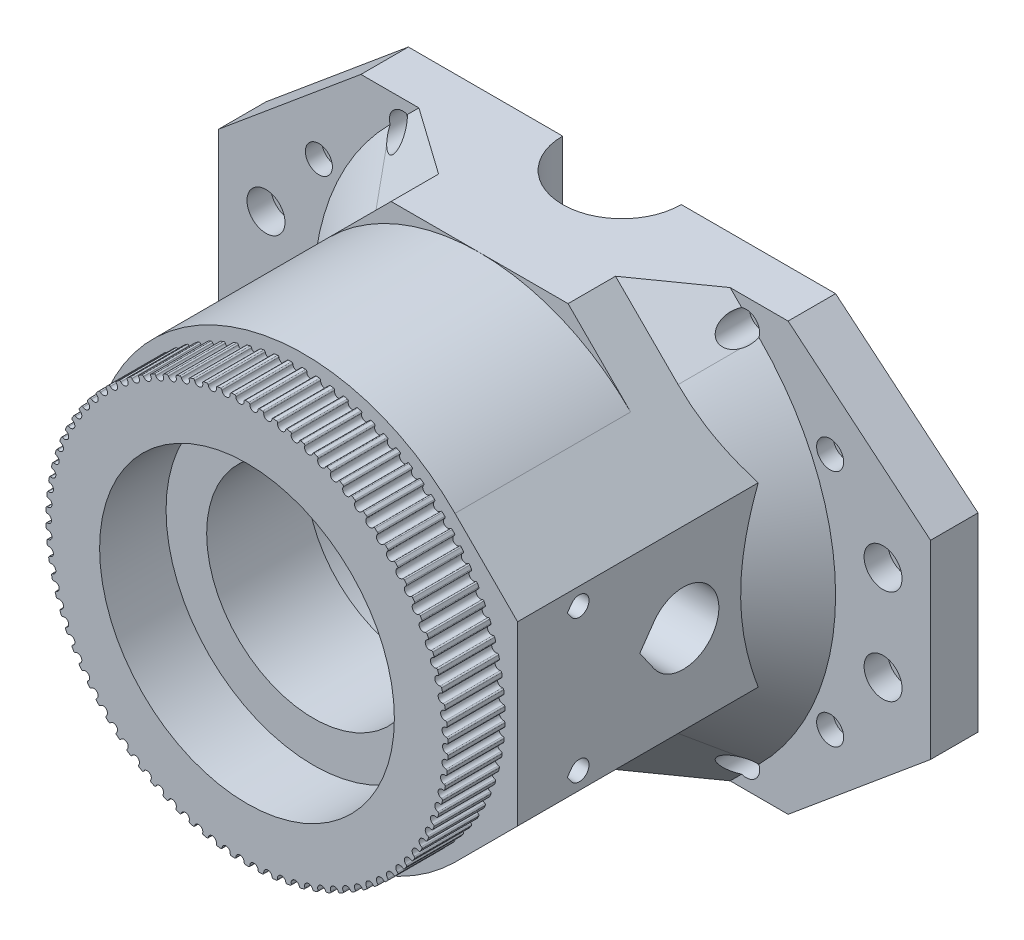
SolidWorks part; units mm, degrees
ref_plane "Front Plane" through (0, 0, 0) normal (1, 0, 0) x (0, 1, 0)
ref_plane "Top Plane" through (0, 0, 0) normal (0, 0, 1) x (0, 1, 0)
ref_plane "Right Plane" through (0, 0, 0) normal (0, 1, 0) x (-1, 0, 0)
sketch "Sketch1" plane through (0, 0, 0) normal (1, 0, 0) x (0, 1, 0)
  line L0 (-45, -80) -> (45, -80)
  line L1 (-31, 0) -> (31, 0)
  line L2 (-31, 0) -> (-31, -14)
  line L3 (-31, -14) -> (31, -14)
  line L4 (31, 0) -> (31, -14)
  line L5 (-31, 0) -> (31, -14) construction
  line L6 (-31, -14) -> (31, 0) construction
  line L7 (-31, -36) -> (31, -36)
  line L8 (-31, -36) -> (-31, -50)
  line L9 (-31, -50) -> (31, -50)
  line L10 (31, -36) -> (31, -50)
  line L11 (-31, -36) -> (31, -50) construction
  line L12 (-31, -50) -> (31, -36) construction
  line L13 (45, -80) -> (45, -1)
  line L14 (45, -1) -> (31, -1)
  line L15 (-31, -1) -> (-45, -1)
  line L16 (-45, -1) -> (-45, -80)
  point P0 (0, -7)
  point P5 (0, -43)
  point P16 (0, 0)
  dimension "D1" = 62
  dimension "D2" = 62
  dimension "D3" = 14
  dimension "D4" = 14
  dimension "D5" = 30
  dimension "D6" = 1
  dimension "D7" = 22
  dimension "D8" = 90
sketch "Sketch2" plane through (0, 0, 0) normal (0, 0, 1) x (0, 1, 0)
  line L0 (-45, 45) -> (-20, 75)
  line L1 (-20, 75) -> (20, 75)
  line L2 (45, 45) -> (-45, 45)
  line L3 (45, 45) -> (45, -45)
  line L4 (45, -45) -> (-45, -45)
  line L5 (-45, 45) -> (-45, -45)
  line L6 (45, 45) -> (-45, -45) construction
  line L7 (45, -45) -> (-45, 45) construction
  line L8 (20, 75) -> (45, 45)
  line L9 (-45, -45) -> (-20, -75)
  line L10 (-20, -75) -> (20, -75)
  line L11 (20, -75) -> (45, -45)
  line L12 (0, 75) -> (0, -75) construction
  line L13 (-45, -18.6396) -> (-18.6396, -45)
  line L14 (-18.6396, 45) -> (-45, 18.6396)
  line L15 (45, 18.6396) -> (18.6396, 45)
  line L16 (18.6396, -45) -> (45, -18.6396)
  circle A0 centre (0, 0) radius 45
  circle A1 centre (0, 0) radius 31.05
  circle A2 centre (0, 0) radius 22.5
  point P15 (0, 0)
  point P27 (0, 0)
  dimension "D1" = 90
  dimension "D2" = 62.1
  dimension "D3" = 45
  dimension "D4" = 150
  dimension "D5" = 40
  dimension "D6" = 4
  dimension "D7" = 45
extrude "Boss-Extrude1" add sketch "Sketch2" against normal up to vertex (80 mm away) from offset 11 contours A0 A1 | A1 A2 region at (-40.3987, 16.7337, 0) region at (0, -30.1718, 0) up to point (0, -45, -80) offset against normal yes
extrude "Boss-Extrude2" add sketch "Sketch2<3>" along normal blind 10 from surface contours A0 L5 L4 | A0 L2 L5 | A0 L4 L3 | A0 L3 L2 | L10 L11 L4 L9 | L8 L1 L0 L2 | A0 L13 L4 | A0 L5 L13 | A0 L4 | A0 L3 | A0 L2 L14 | A0 L14 L5 | A0 L3 L15 | A0 L15 L2 region at (-58.0769, 0, 0) region at (-36.2132, -36.2132, 0) region at (-42.2926, -17.5182, 0) region at (-17.5182, -42.2926, 0) region at (-42.2926, 17.5182, 0) region at (17.5182, -42.2926, 0) region at (-36.2132, 36.2132, 0) region at (-17.5182, 42.2926, 0) region at (36.2132, -36.2132, 0) region at (42.2926, -17.5182, 0) region at (17.5182, 42.2926, 0) region at (58.0769, 0, 0) region at (42.2926, 17.5182, 0) region at (36.2132, 36.2132, 0) starting at face at (45, 0, -80)
sketch "Sketch2<3>" plane through (0, 0, 0) normal (0, 0, 1) x (0, 1, 0) same geometry as "Sketch2"
extrude "Boss-Extrude4" add sketch "Sketch2<6>" along normal blind 20 from surface contours A0 L5 | A0 L5 L13 | A0 L16 L3 | A0 L3 L15 region at (-17.5182, -42.2926, 0) region at (17.5182, -42.2926, 0) region at (-17.5182, 42.2926, 0) region at (17.5182, 42.2926, 0) starting at face at (-47.5, 0, -70)
sketch "Sketch2<6>" plane through (0, 0, 0) normal (0, 0, 1) x (0, 1, 0) same geometry as "Sketch2"
sketch "Sketch5" plane through (0, -45, 0) normal (0, -1, 0) x (1, 0, 0)
  line L0 (-45, -80) -> (45, -80) construction
  circle A0 centre (0, -80) radius 12.5
  line M9 (-45, -80) -> (45, -80)
  dimension "D1" = 25
extrude "Cut-Extrude3" cut sketch "Sketch5" against normal through all contours A0 M9 region at (0, -45, -74.6948)
sketch "Sketch6" plane through (0, 0, -70) normal (0, 0, 1) x (1, 0, 0)
  line L0 (-65, 10) -> (-65, -10) construction
  line L1 (0, 0) -> (-99.7082, 0) construction
  line L2 (65, 10) -> (65, -10) construction
  line L3 (75, -20) -> (75, 20) construction
  line L4 (-75, -20) -> (-75, 20) construction
  circle A0 centre (65, 10) radius 4
  circle A1 centre (65, 10) radius 2.05
  circle A2 centre (-65, 10) radius 2.05
  circle A3 centre (-65, 10) radius 4
  circle A4 centre (-65, -10) radius 2.05
  circle A5 centre (-65, -10) radius 4
  circle A6 centre (65, -10) radius 2.05
  circle A7 centre (65, -10) radius 4
  point P3 (-65, 0)
  point P9 (65, 0)
  dimension "D4" = 8
  dimension "D5" = 4.1
  dimension "D1" = 20
  dimension "D2" = 10
  dimension "D3" = 10
  dimension "D6" = 2
  dimension "D7" = 2
extrude "Cut-Extrude4" cut sketch "Sketch6" against normal through all contours A1 | A4 | A2 | A6
extrude "Cut-Extrude5" cut sketch "Sketch6<4>" against normal blind 5
sketch "Sketch6<4>" plane through (0, 0, -70) normal (0, 0, 1) x (1, 0, 0) same geometry as "Sketch6"
extrude "Cut-Extrude1" cut sketch "Sketch2<4>" against normal blind 15 contours A1
sketch "Sketch2<4>" plane through (0, 0, 0) normal (0, 0, 1) x (0, 1, 0) same geometry as "Sketch2"
extrude "Cut-Extrude2" cut sketch "Sketch2<5>" against normal through all from vertex contours A1 starting at point (0, -31, -36)
sketch "Sketch2<5>" plane through (0, 0, 0) normal (0, 0, 1) x (0, 1, 0) same geometry as "Sketch2"
sketch "Sketch7" plane through (0, 0, -70) normal (0, 0, 1) x (1, 0, 0)
  line L0 (-75, 20) -> (75, 20) construction
  line L1 (-45, 45) -> (-18.6396, 45) construction
  line L2 (-45, 45) -> (0, 45) construction
  line L3 (-30, 45) -> (-60, 20) construction
  line L4 (-75, 20) -> (-45, 45) construction
  line L5 (0, 13.0372) -> (0, -13.0372) construction
  line L6 (-13.0372, 0) -> (13.0372, 0) construction
  line L7 (30, 45) -> (60, 20) construction
  line L8 (30, -45) -> (60, -20) construction
  line L9 (-30, -45) -> (-60, -20) construction
  circle A0 centre (-53.8542, 25.1215) radius 1.6
  circle A1 centre (-53.8542, 25.1215) radius 2.85
  circle A2 centre (-36.1458, 39.8785) radius 2.85
  circle A3 centre (-36.1458, 39.8785) radius 1.6
  circle A4 centre (36.1458, 39.8785) radius 1.6
  circle A5 centre (36.1458, 39.8785) radius 2.85
  circle A6 centre (53.8542, 25.1215) radius 2.85
  circle A7 centre (53.8542, 25.1215) radius 1.6
  circle A8 centre (53.8542, -25.1215) radius 1.6
  circle A9 centre (53.8542, -25.1215) radius 2.85
  circle A10 centre (36.1458, -39.8785) radius 2.85
  circle A11 centre (36.1458, -39.8785) radius 1.6
  circle A12 centre (-36.1458, -39.8785) radius 1.6
  circle A13 centre (-36.1458, -39.8785) radius 2.85
  circle A14 centre (-53.8542, -25.1215) radius 2.85
  circle A15 centre (-53.8542, -25.1215) radius 1.6
  circle A16 centre (-36.1458, -39.8785) radius 5.5
  circle A17 centre (36.1458, -39.8785) radius 5.5
  point P23 (0, 0)
  point P26 (0, 0)
  dimension "D2" = 5.7
  dimension "D3" = 3.2
  dimension "D6" = 3.2
  dimension "D7" = 5.7
  dimension "D8" = 11
  dimension "D9" = 11
  dimension "D1" = 15
  dimension "D4" = 8
  dimension "D5" = 8
extrude "Cut-Extrude6" cut sketch "Sketch7" against normal through all contours A15 | A0 | A3 | A4 | A7 | A8 | A11 | A12
extrude "Cut-Extrude7" cut sketch "Sketch7<3>" against normal blind 3.5 contours A14 | A1 | A2 | A5 | A6 | A9 | A10 | A13
sketch "Sketch7<3>" plane through (0, 0, -70) normal (0, 0, 1) x (1, 0, 0) same geometry as "Sketch7"
chamfer "Chamfer2" distance 10 angle 45 6 edges at (25.2297, -38.4099, -70) (25.2297, 38.4099, -70) (45, 0, -70) (-25.2297, 38.4099, -70) (-25.2297, -38.4099, -70) (-45, 0, -70)
extrude "Boss-Extrude6" add sketch "Sketch2<7>" against normal up to surface (70 mm away) from surface contours A0 L13 L4 | A0 L4 L16 region at (42.2926, -17.5182, 0) region at (42.2926, 17.5182, 0) up to face at (56.7042, -25.1215, -70) starting at face at (31.05, 0, -11)
sketch "Sketch2<7>" plane through (0, 0, 0) normal (0, 0, 1) x (0, 1, 0) same geometry as "Sketch2"
sketch "Sketch8" plane through (45, 0, 0) normal (1, 0, 0) x (0, 1, 0)
  line L0 (-15, -26) -> (-9.9, -26) construction
  line L1 (15, -26) -> (20.2, -26) construction
  line L2 (-15, -26) -> (-20.2, -26) construction
  line L3 (-9.9, -26) -> (15, -26) construction
  line L4 (-9.9, -26) -> (-9.9, -11) construction
  line L5 (18.6396, -11) -> (-18.6396, -11) construction
  line L6 (-20.2, -26) -> (-20.2, -11)
  line L7 (-31.8198, -11) -> (-18.6396, -11) construction
  line L8 (20.2, -26) -> (20.2, -11)
  line L9 (18.6396, -11) -> (31.8198, -11) construction
  line L10 (-14.0823, -24.6894) -> (-15, -24.0468)
  line L11 (-16.1758, -24.3207) -> (-15, -23.4974)
  line L12 (-15.9177, -24.6894) -> (-15, -24.0468)
  line L13 (-13.8242, -24.3207) -> (-15, -23.4974)
  line L14 (-15, -26) -> (-15, -23.4974) construction
  line L15 (16.1758, -24.3207) -> (15, -23.4974)
  line L16 (15, -26) -> (15, -23.4974) construction
  line L17 (14.0823, -24.6894) -> (15, -24.0468)
  line L18 (13.8242, -24.3207) -> (15, -23.4974)
  line L19 (15.9177, -24.6894) -> (15, -24.0468)
  line L20 (-20.2, -11) -> (20.2, -11)
  line L21 (-20.2, -26) -> (-20.2, -32.9)
  line L22 (20.2, -26) -> (20.2, -32.9)
  line L23 (-20.2, -32.9) -> (20.2, -32.9)
  line L24 (0, -47.9) -> (0, -38.7442) construction
  line L25 (-4.3018, -41.7564) -> (0, -38.7442)
  line L26 (4.3018, -41.7564) -> (0, -38.7442)
  arc A0 (-16.1758, -24.3207) -> (-13.8242, -24.3207) centre (-15, -26) ccw
  arc A1 (-15.9177, -24.6894) -> (-14.0823, -24.6894) centre (-15, -26) ccw
  arc A2 (14.0823, -24.6894) -> (15.9177, -24.6894) centre (15, -26) ccw
  arc A3 (13.8242, -24.3207) -> (16.1758, -24.3207) centre (15, -26) ccw
  arc A4 (-4.3018, -41.7564) -> (4.3018, -41.7564) centre (0, -47.9) ccw
  point P29 (0, -11)
  dimension "D6" = 3.2
  dimension "D7" = 4.1
  dimension "D10" = 3.2
  dimension "D11" = 4.1
  dimension "D15" = 15
  dimension "D1" = 15
  dimension "D2" = 24.9
  dimension "D3" = 5.2
  dimension "D4" = 5.1
  dimension "D5" = 5.2
  dimension "D8" = 55
  dimension "D9" = 55
  dimension "D12" = 55
  dimension "D13" = 55
  dimension "D14" = 6.9
  dimension "D16" = 15
  dimension "D17" = 55
sketch "Sketch3" plane through (0, 0, -11) normal (0, 0, 1) x (1, 0, 0)
  line L0 (0, 0) -> (0, 42.3568)
  line L1 (0, 0) -> (1.4374, 41.1617) construction
  line L2 (0, 0) -> (2.9547, 42.2537)
  line L3 (1.4374, 41.1617) -> (1.4678, 42.0312) construction
  arc A0 (0.6589, 42.3517) -> (2.297, 42.2945) centre (1.4678, 42.0312) ccw
  arc A1 (0, 42.3568) -> (0.6589, 42.3517) centre (0, 0) cw
  arc A2 (2.297, 42.2945) -> (2.9547, 42.2537) centre (0, 0) cw
  arc A3 (0, 31.05) -> (2.1659, 30.9744) centre (0, 0) cw
  circle A4 centre (0, 0) radius 31.05 construction
  circle M5 centre (0, 0) radius 31.05
  dimension "D1" = 42.3568
  dimension "D2" = 2
  dimension "D3" = 2
  dimension "D4" = 42.3568
  dimension "D5" = 41.1868
  dimension "D6" = 0.87
extrude "Boss-Extrude3" add sketch "Sketch3" along normal up to vertex (10 mm away) contours A2 A0 A1 L0 L2 M5 region at (1.2803, 36.6619, -11) up to point (0, 45, -1)
fillet "Fillet1" radius 0.26 2 edges at (2.297, 42.2945, -6) (0.6589, 42.3517, -6)
pattern_circular "CirPattern1" count 90 over 360 about axis through (0, 0, -80) along (0, 0, 1) of "Fillet1", "Boss-Extrude3" reverse direction yes
extrude "Cut-Extrude9" cut sketch "Sketch8" against normal blind 7 contours A0 L13 L11 | A3 L15 L18
extrude "Cut-Extrude10" cut sketch "Sketch8<3>" against normal blind 3 from surface contours A1 L10 L12 | A2 L19 L17 starting at face at (38, -15, -25.2894)
sketch "Sketch8<3>" plane through (45, 0, 0) normal (1, 0, 0) x (0, 1, 0) same geometry as "Sketch8"
extrude "Cut-Extrude11" cut sketch "Sketch8<4>" against normal blind 45 contours A4 L26 L25
sketch "Sketch8<4>" plane through (45, 0, 0) normal (1, 0, 0) x (0, 1, 0) same geometry as "Sketch8"
sketch "Sketch11" plane through (0, 0, -11) normal (0, 0, 1) x (1, 0, 0)
  line L0 (45, -18.6396) -> (45, 18.6396) construction
  line L1 (45, 18.6396) -> (31.8198, 31.8198) construction
  line L2 (31.8198, -31.8198) -> (45, -18.6396) construction
  line L3 (45, -18.6396) -> (45, 18.6396)
  line L4 (45, 18.6396) -> (31.8198, 31.8198)
  line L5 (31.8198, -31.8198) -> (45, -18.6396)
  arc A0 (31.8198, 31.8198) -> (31.8198, -31.8198) centre (0, 0) ccw construction
  arc A1 (0.3417, 42.3555) -> (-0.3417, 42.3555) centre (0, 0) ccw construction
  arc A2 (-0.3417, 42.3555) -> (-0.5992, 42.0807) centre (-0.3396, 42.0955) ccw construction
  arc A3 (-2.3377, 42.02) -> (-0.5992, 42.0807) centre (-1.4678, 42.0312) ccw construction
  arc A4 (-2.3377, 42.02) -> (-2.6137, 42.2761) centre (-2.5977, 42.0166) ccw construction
  arc A5 (-2.6137, 42.2761) -> (-3.2954, 42.2284) centre (0, 0) ccw construction
  arc A6 (-3.2954, 42.2284) -> (-3.5331, 41.9364) centre (-3.2752, 41.9692) ccw construction
  arc A7 (-5.2632, 41.7545) -> (-3.5331, 41.9364) centre (-4.3961, 41.8264) ccw construction
  arc A8 (-5.2632, 41.7545) -> (-5.5564, 41.9908) centre (-5.5223, 41.7331) ccw construction
  arc A9 (-5.5564, 41.9908) -> (-6.2331, 41.8957) centre (0, 0) ccw construction
  arc A10 (-6.2331, 41.8957) -> (-6.4498, 41.5878) centre (-6.1948, 41.6385) ccw construction
  arc A11 (-8.163, 41.2857) -> (-6.4498, 41.5878) centre (-7.3031, 41.4179) ccw construction
  arc A12 (-8.163, 41.2857) -> (-8.472, 41.5009) centre (-8.42, 41.2462) ccw construction
  arc A13 (-8.472, 41.5009) -> (-9.1404, 41.3588) centre (0, 0) ccw construction
  arc A14 (-9.1404, 41.3588) -> (-9.3351, 41.0365) centre (-9.0843, 41.105) ccw construction
  arc A15 (-11.023, 40.6157) -> (-9.3351, 41.0365) centre (-10.1745, 40.8076) ccw construction
  arc A16 (-11.023, 40.6157) -> (-11.3463, 40.8089) centre (-11.2766, 40.5584) ccw construction
  arc A17 (-11.3463, 40.8089) -> (-12.0032, 40.6205) centre (0, 0) ccw construction
  arc A18 (-12.0032, 40.6205) -> (-12.175, 40.2854) centre (-11.9295, 40.3712) ccw construction
  arc A19 (-13.8294, 39.7478) -> (-12.175, 40.2854) centre (-12.9963, 39.9984) ccw construction
  arc A20 (-13.8294, 39.7478) -> (-14.1653, 39.918) centre (-14.0784, 39.6729) ccw construction
  arc A21 (-14.1653, 39.918) -> (-14.8075, 39.6842) centre (0, 0) ccw construction
  arc A22 (-14.8075, 39.6842) -> (-14.9555, 39.338) centre (-14.7166, 39.4407) ccw construction
  arc A23 (-16.5684, 38.6863) -> (-14.9555, 39.338) centre (-15.7548, 38.9944) ccw construction
  arc A24 (-16.5684, 38.6863) -> (-16.9154, 38.8326) centre (-16.8115, 38.5942) ccw construction
  arc A25 (-16.9154, 38.8326) -> (-17.5397, 38.5547) centre (0, 0) ccw construction
  arc A26 (-17.5397, 38.5547) -> (-17.6631, 38.1989) centre (-17.432, 38.318) ccw construction
  arc A27 (-19.2266, 37.4363) -> (-17.6631, 38.1989) centre (-18.4365, 37.8004) ccw construction
  arc A28 (-19.2266, 37.4363) -> (-19.583, 37.5581) centre (-19.4628, 37.3275) ccw construction
  arc A29 (-19.583, 37.5581) -> (-20.1864, 37.2372) centre (0, 0) ccw construction
  arc A30 (-20.1864, 37.2372) -> (-20.2847, 36.8737) centre (-20.0625, 37.0087) ccw construction
  arc A31 (-21.7912, 36.004) -> (-20.2847, 36.8737) centre (-21.0284, 36.4223) ccw construction
  arc A32 (-21.7912, 36.004) -> (-22.1552, 36.1005) centre (-22.0192, 35.8789) ccw construction
  arc A33 (-22.1552, 36.1005) -> (-22.7347, 35.7384) centre (0, 0) ccw construction
  arc A34 (-22.7347, 35.7384) -> (-22.8075, 35.3689) centre (-22.5952, 35.519) ccw construction
  arc A35 (-24.2497, 34.3962) -> (-22.8075, 35.3689) centre (-23.5179, 34.8667) ccw construction
  arc A36 (-24.2497, 34.3962) -> (-24.6195, 34.4671) centre (-24.4684, 34.2556) ccw construction
  arc A37 (-24.6195, 34.4671) -> (-25.1723, 34.0654) centre (0, 0) ccw construction
  arc A38 (-25.1723, 34.0654) -> (-25.2191, 33.6918) centre (-25.0178, 33.8563) ccw construction
  arc A39 (-26.59, 32.6208) -> (-25.2191, 33.6918) centre (-25.8928, 33.1412) ccw construction
  arc A40 (-26.59, 32.6208) -> (-26.9638, 32.6658) centre (-26.7983, 32.4653) ccw construction
  arc A41 (-26.9638, 32.6658) -> (-27.4873, 32.2265) centre (0, 0) ccw construction
  arc A42 (-27.4873, 32.2265) -> (-27.5079, 31.8505) centre (-27.3186, 32.0287) ccw construction
  arc A43 (-28.8007, 30.6865) -> (-27.5079, 31.8505) centre (-28.1415, 31.2543) ccw construction
  arc A44 (-28.8007, 30.6865) -> (-29.1768, 30.7053) centre (-28.9977, 30.5168) ccw construction
  arc A45 (-29.1768, 30.7053) -> (-29.6684, 30.2306) centre (0, 0) ccw construction
  arc A46 (-29.6684, 30.2306) -> (-29.6627, 29.8541) centre (-29.4862, 30.045) ccw construction
  arc A47 (-30.8711, 28.6027) -> (-29.6627, 29.8541) centre (-30.2532, 29.2151) ccw construction
  arc A48 (-30.8711, 28.6027) -> (-31.2476, 28.5953) centre (-31.0558, 28.4197) ccw construction
  arc A49 (-31.2476, 28.5953) -> (-31.7049, 28.0874) centre (0, 0) ccw construction
  arc A50 (-31.7049, 28.0874) -> (-31.673, 27.7122) centre (-31.5103, 27.915) ccw construction
  arc A51 (-32.7911, 26.3796) -> (-31.673, 27.7122) centre (-32.2174, 27.0336) ccw construction
  arc A52 (-32.7911, 26.3796) -> (-33.1662, 26.3459) centre (-32.9626, 26.1842) ccw construction
  arc A53 (-33.1662, 26.3459) -> (-33.5869, 25.8074) centre (0, 0) ccw construction
  arc A54 (-33.5869, 25.8074) -> (-33.5289, 25.4353) centre (-33.3808, 25.649) ccw construction
  arc A55 (-34.5514, 24.028) -> (-33.5289, 25.4353) centre (-34.0247, 24.7204) ccw construction
  arc A56 (-34.5514, 24.028) -> (-34.9232, 23.9681) centre (-34.7088, 23.821) ccw construction
  arc A57 (-34.9232, 23.9681) -> (-35.3053, 23.4016) centre (0, 0) ccw construction
  arc A58 (-35.3053, 23.4016) -> (-35.2215, 23.0345) centre (-35.0886, 23.258) ccw construction
  arc A59 (-36.1434, 21.5592) -> (-35.2215, 23.0345) centre (-35.6662, 22.2867) ccw construction
  arc A60 (-36.1434, 21.5592) -> (-36.5101, 21.4736) centre (-36.2859, 21.3418) ccw construction
  arc A61 (-36.5101, 21.4736) -> (-36.8517, 20.8818) centre (0, 0) ccw construction
  arc A62 (-36.8517, 20.8818) -> (-36.7425, 20.5214) centre (-36.6255, 20.7536) ccw construction
  arc A63 (-37.5592, 18.9855) -> (-36.7425, 20.5214) centre (-37.134, 19.7445) ccw construction
  arc A64 (-37.5592, 18.9855) -> (-37.919, 18.8745) centre (-37.6863, 18.7587) ccw construction
  arc A65 (-37.919, 18.8745) -> (-38.2186, 18.2603) centre (0, 0) ccw construction
  arc A66 (-38.2186, 18.2603) -> (-38.0845, 17.9084) centre (-37.984, 18.1482) ccw construction
  arc A67 (-38.7921, 16.3192) -> (-38.0845, 17.9084) centre (-38.4208, 17.1061) ccw construction
  arc A68 (-38.7921, 16.3192) -> (-39.1433, 16.1834) centre (-38.903, 16.0841) ccw construction
  arc A69 (-39.1433, 16.1834) -> (-39.3993, 15.5498) centre (0, 0) ccw construction
  arc A70 (-39.3993, 15.5498) -> (-39.241, 15.2082) centre (-39.1574, 15.4544) ccw construction
  arc A71 (-39.836, 13.5735) -> (-39.241, 15.2082) centre (-39.5205, 14.3843) ccw construction
  arc A72 (-39.836, 13.5735) -> (-40.1768, 13.4135) centre (-39.9302, 13.3312) ccw construction
  arc A73 (-40.1768, 13.4135) -> (-40.388, 12.7636) centre (0, 0) ccw construction
  arc A74 (-40.388, 12.7636) -> (-40.2063, 12.4338) centre (-40.1401, 12.6852) ccw construction
  arc A75 (-40.6858, 10.7616) -> (-40.2063, 12.4338) centre (-40.4276, 11.5924) ccw construction
  arc A76 (-40.6858, 10.7616) -> (-41.0147, 10.5783) centre (-40.7629, 10.5133) ccw construction
  arc A77 (-41.0147, 10.5783) -> (-41.18, 9.9152) centre (0, 0) ccw construction
  arc A78 (-41.18, 9.9152) -> (-40.9757, 9.5989) centre (-40.9272, 9.8543) ccw construction
  arc A79 (-41.3373, 7.8973) -> (-40.9757, 9.5989) centre (-41.1378, 8.7441) ccw construction
  arc A80 (-41.3373, 7.8973) -> (-41.6526, 7.6914) centre (-41.397, 7.6442) ccw construction
  arc A81 (-41.6526, 7.6914) -> (-41.7713, 7.0185) centre (0, 0) ccw construction
  arc A82 (-41.7713, 7.0185) -> (-41.5454, 6.7172) centre (-41.5149, 6.9754) ccw construction
  arc A83 (-41.7875, 4.9945) -> (-41.5454, 6.7172) centre (-41.6475, 5.8532) ccw construction
  arc A84 (-41.7875, 4.9945) -> (-42.0877, 4.7672) centre (-41.8294, 4.7379) ccw construction
  arc A85 (-42.0877, 4.7672) -> (-42.1591, 4.0875) centre (0, 0) ccw construction
  arc A86 (-42.1591, 4.0875) -> (-41.9128, 3.8027) centre (-41.9004, 4.0624) ccw construction
  arc A87 (-42.0341, 2.0674) -> (-41.9128, 3.8027) centre (-41.9544, 2.9337) ccw construction
  arc A88 (-42.0341, 2.0674) -> (-42.3177, 1.8197) centre (-42.058, 1.8085) ccw construction
  arc A89 (-42.3177, 1.8197) -> (-42.3416, 1.1367) centre (0, 0) ccw construction
  arc A90 (-42.3416, 1.1367) -> (-42.076, 0.8698) centre (-42.0817, 1.1297) ccw construction
  arc A91 (-42.076, -0.8698) -> (-42.076, 0.8698) centre (-42.0568, 0) ccw construction
  arc A92 (-42.076, -0.8698) -> (-42.3416, -1.1367) centre (-42.0817, -1.1297) ccw construction
  arc A93 (-42.3416, -1.1367) -> (-42.3177, -1.8197) centre (0, 0) ccw construction
  arc A94 (-42.3177, -1.8197) -> (-42.0341, -2.0674) centre (-42.058, -1.8085) ccw construction
  arc A95 (-41.9128, -3.8027) -> (-42.0341, -2.0674) centre (-41.9544, -2.9337) ccw construction
  arc A96 (-41.9128, -3.8027) -> (-42.1591, -4.0875) centre (-41.9004, -4.0624) ccw construction
  arc A97 (-42.1591, -4.0875) -> (-42.0877, -4.7672) centre (0, 0) ccw construction
  arc A98 (-42.0877, -4.7672) -> (-41.7875, -4.9945) centre (-41.8294, -4.7379) ccw construction
  arc A99 (-41.5454, -6.7172) -> (-41.7875, -4.9945) centre (-41.6475, -5.8532) ccw construction
  arc A100 (-41.5454, -6.7172) -> (-41.7713, -7.0185) centre (-41.5149, -6.9754) ccw construction
  arc A101 (-41.7713, -7.0185) -> (-41.6526, -7.6914) centre (0, 0) ccw construction
  arc A102 (-41.6526, -7.6914) -> (-41.3373, -7.8973) centre (-41.397, -7.6442) ccw construction
  arc A103 (-40.9757, -9.5989) -> (-41.3373, -7.8973) centre (-41.1378, -8.7441) ccw construction
  arc A104 (-40.9757, -9.5989) -> (-41.18, -9.9152) centre (-40.9272, -9.8543) ccw construction
  arc A105 (-41.18, -9.9152) -> (-41.0147, -10.5783) centre (0, 0) ccw construction
  arc A106 (-41.0147, -10.5783) -> (-40.6858, -10.7616) centre (-40.7629, -10.5133) ccw construction
  arc A107 (-40.2063, -12.4338) -> (-40.6858, -10.7616) centre (-40.4276, -11.5924) ccw construction
  arc A108 (-40.2063, -12.4338) -> (-40.388, -12.7636) centre (-40.1401, -12.6852) ccw construction
  arc A109 (-40.388, -12.7636) -> (-40.1768, -13.4135) centre (0, 0) ccw construction
  arc A110 (-40.1768, -13.4135) -> (-39.836, -13.5735) centre (-39.9302, -13.3312) ccw construction
  arc A111 (-39.241, -15.2082) -> (-39.836, -13.5735) centre (-39.5205, -14.3843) ccw construction
  arc A112 (-39.241, -15.2082) -> (-39.3993, -15.5498) centre (-39.1574, -15.4544) ccw construction
  arc A113 (-39.3993, -15.5498) -> (-39.1433, -16.1834) centre (0, 0) ccw construction
  arc A114 (-39.1433, -16.1834) -> (-38.7921, -16.3192) centre (-38.903, -16.0841) ccw construction
  arc A115 (-38.0845, -17.9084) -> (-38.7921, -16.3192) centre (-38.4208, -17.1061) ccw construction
  arc A116 (-38.0845, -17.9084) -> (-38.2186, -18.2603) centre (-37.984, -18.1482) ccw construction
  arc A117 (-38.2186, -18.2603) -> (-37.919, -18.8745) centre (0, 0) ccw construction
  arc A118 (-37.919, -18.8745) -> (-37.5592, -18.9855) centre (-37.6863, -18.7587) ccw construction
  arc A119 (-36.7425, -20.5214) -> (-37.5592, -18.9855) centre (-37.134, -19.7445) ccw construction
  arc A120 (-36.7425, -20.5214) -> (-36.8517, -20.8818) centre (-36.6255, -20.7536) ccw construction
  arc A121 (-36.8517, -20.8818) -> (-36.5101, -21.4736) centre (0, 0) ccw construction
  arc A122 (-36.5101, -21.4736) -> (-36.1434, -21.5592) centre (-36.2859, -21.3418) ccw construction
  arc A123 (-35.2215, -23.0345) -> (-36.1434, -21.5592) centre (-35.6662, -22.2867) ccw construction
  arc A124 (-35.2215, -23.0345) -> (-35.3053, -23.4016) centre (-35.0886, -23.258) ccw construction
  arc A125 (-35.3053, -23.4016) -> (-34.9232, -23.9681) centre (0, 0) ccw construction
  arc A126 (-34.9232, -23.9681) -> (-34.5514, -24.028) centre (-34.7088, -23.821) ccw construction
  arc A127 (-33.5289, -25.4353) -> (-34.5514, -24.028) centre (-34.0247, -24.7204) ccw construction
  arc A128 (-33.5289, -25.4353) -> (-33.5869, -25.8074) centre (-33.3808, -25.649) ccw construction
  arc A129 (-33.5869, -25.8074) -> (-33.1662, -26.3459) centre (0, 0) ccw construction
  arc A130 (-33.1662, -26.3459) -> (-32.7911, -26.3796) centre (-32.9626, -26.1842) ccw construction
  arc A131 (-31.673, -27.7122) -> (-32.7911, -26.3796) centre (-32.2174, -27.0336) ccw construction
  arc A132 (-31.673, -27.7122) -> (-31.7049, -28.0874) centre (-31.5103, -27.915) ccw construction
  arc A133 (-31.7049, -28.0874) -> (-31.2476, -28.5953) centre (0, 0) ccw construction
  arc A134 (-31.2476, -28.5953) -> (-30.8711, -28.6027) centre (-31.0558, -28.4197) ccw construction
  arc A135 (-29.6627, -29.8541) -> (-30.8711, -28.6027) centre (-30.2532, -29.2151) ccw construction
  arc A136 (-29.6627, -29.8541) -> (-29.6684, -30.2306) centre (-29.4862, -30.045) ccw construction
  arc A137 (-29.6684, -30.2306) -> (-29.1768, -30.7053) centre (0, 0) ccw construction
  arc A138 (-29.1768, -30.7053) -> (-28.8007, -30.6865) centre (-28.9977, -30.5168) ccw construction
  arc A139 (-27.5079, -31.8505) -> (-28.8007, -30.6865) centre (-28.1415, -31.2543) ccw construction
  arc A140 (-27.5079, -31.8505) -> (-27.4873, -32.2265) centre (-27.3186, -32.0287) ccw construction
  arc A141 (-27.4873, -32.2265) -> (-26.9638, -32.6658) centre (0, 0) ccw construction
  arc A142 (-26.9638, -32.6658) -> (-26.59, -32.6208) centre (-26.7983, -32.4653) ccw construction
  arc A143 (-25.2191, -33.6918) -> (-26.59, -32.6208) centre (-25.8928, -33.1412) ccw construction
  arc A144 (-25.2191, -33.6918) -> (-25.1723, -34.0654) centre (-25.0178, -33.8563) ccw construction
  arc A145 (-25.1723, -34.0654) -> (-24.6195, -34.4671) centre (0, 0) ccw construction
  arc A146 (-24.6195, -34.4671) -> (-24.2497, -34.3962) centre (-24.4684, -34.2556) ccw construction
  arc A147 (-22.8075, -35.3689) -> (-24.2497, -34.3962) centre (-23.5179, -34.8667) ccw construction
  arc A148 (-22.8075, -35.3689) -> (-22.7347, -35.7384) centre (-22.5952, -35.519) ccw construction
  arc A149 (-22.7347, -35.7384) -> (-22.1552, -36.1005) centre (0, 0) ccw construction
  arc A150 (-22.1552, -36.1005) -> (-21.7912, -36.004) centre (-22.0192, -35.8789) ccw construction
  arc A151 (-20.2847, -36.8737) -> (-21.7912, -36.004) centre (-21.0284, -36.4223) ccw construction
  arc A152 (-20.2847, -36.8737) -> (-20.1864, -37.2372) centre (-20.0625, -37.0087) ccw construction
  arc A153 (-20.1864, -37.2372) -> (-19.583, -37.5581) centre (0, 0) ccw construction
  arc A154 (-19.583, -37.5581) -> (-19.2266, -37.4363) centre (-19.4628, -37.3275) ccw construction
  arc A155 (-17.6631, -38.1989) -> (-19.2266, -37.4363) centre (-18.4365, -37.8004) ccw construction
  arc A156 (-17.6631, -38.1989) -> (-17.5397, -38.5547) centre (-17.432, -38.318) ccw construction
  arc A157 (-17.5397, -38.5547) -> (-16.9154, -38.8326) centre (0, 0) ccw construction
  arc A158 (-16.9154, -38.8326) -> (-16.5684, -38.6863) centre (-16.8115, -38.5942) ccw construction
  arc A159 (-14.9555, -39.338) -> (-16.5684, -38.6863) centre (-15.7548, -38.9944) ccw construction
  arc A160 (-14.9555, -39.338) -> (-14.8075, -39.6842) centre (-14.7166, -39.4407) ccw construction
  arc A161 (-14.8075, -39.6842) -> (-14.1653, -39.918) centre (0, 0) ccw construction
  arc A162 (-14.1653, -39.918) -> (-13.8294, -39.7478) centre (-14.0784, -39.6729) ccw construction
  arc A163 (-12.175, -40.2854) -> (-13.8294, -39.7478) centre (-12.9963, -39.9984) ccw construction
  arc A164 (-12.175, -40.2854) -> (-12.0032, -40.6205) centre (-11.9295, -40.3712) ccw construction
  arc A165 (-12.0032, -40.6205) -> (-11.3463, -40.8089) centre (0, 0) ccw construction
  arc A166 (-11.3463, -40.8089) -> (-11.023, -40.6157) centre (-11.2766, -40.5584) ccw construction
  arc A167 (-9.3351, -41.0365) -> (-11.023, -40.6157) centre (-10.1745, -40.8076) ccw construction
  arc A168 (-9.3351, -41.0365) -> (-9.1404, -41.3588) centre (-9.0843, -41.105) ccw construction
  arc A169 (-9.1404, -41.3588) -> (-8.472, -41.5009) centre (0, 0) ccw construction
  arc A170 (-8.472, -41.5009) -> (-8.163, -41.2857) centre (-8.42, -41.2462) ccw construction
  arc A171 (-6.4498, -41.5878) -> (-8.163, -41.2857) centre (-7.3031, -41.4179) ccw construction
  arc A172 (-6.4498, -41.5878) -> (-6.2331, -41.8957) centre (-6.1948, -41.6385) ccw construction
  arc A173 (-6.2331, -41.8957) -> (-5.5564, -41.9908) centre (0, 0) ccw construction
  arc A174 (-5.5564, -41.9908) -> (-5.2632, -41.7545) centre (-5.5223, -41.7331) ccw construction
  arc A175 (-3.5331, -41.9364) -> (-5.2632, -41.7545) centre (-4.3961, -41.8264) ccw construction
  arc A176 (-3.5331, -41.9364) -> (-3.2954, -42.2284) centre (-3.2752, -41.9692) ccw construction
  arc A177 (-3.2954, -42.2284) -> (-2.6137, -42.2761) centre (0, 0) ccw construction
  arc A178 (-2.6137, -42.2761) -> (-2.3377, -42.02) centre (-2.5977, -42.0166) ccw construction
  arc A179 (-0.5992, -42.0807) -> (-2.3377, -42.02) centre (-1.4678, -42.0312) ccw construction
  arc A180 (-0.5992, -42.0807) -> (-0.3417, -42.3555) centre (-0.3396, -42.0955) ccw construction
  arc A181 (-0.3417, -42.3555) -> (0.3417, -42.3555) centre (0, 0) ccw construction
  arc A182 (0.3417, -42.3555) -> (0.5992, -42.0807) centre (0.3396, -42.0955) ccw construction
  arc A183 (2.3377, -42.02) -> (0.5992, -42.0807) centre (1.4678, -42.0312) ccw construction
  arc A184 (2.3377, -42.02) -> (2.6137, -42.2761) centre (2.5977, -42.0166) ccw construction
  arc A185 (2.6137, -42.2761) -> (3.2954, -42.2284) centre (0, 0) ccw construction
  arc A186 (3.2954, -42.2284) -> (3.5331, -41.9364) centre (3.2752, -41.9692) ccw construction
  arc A187 (5.2632, -41.7545) -> (3.5331, -41.9364) centre (4.3961, -41.8264) ccw construction
  arc A188 (5.2632, -41.7545) -> (5.5564, -41.9908) centre (5.5223, -41.7331) ccw construction
  arc A189 (5.5564, -41.9908) -> (6.2331, -41.8957) centre (0, 0) ccw construction
  arc A190 (6.2331, -41.8957) -> (6.4498, -41.5878) centre (6.1948, -41.6385) ccw construction
  arc A191 (8.163, -41.2857) -> (6.4498, -41.5878) centre (7.3031, -41.4179) ccw construction
  arc A192 (8.163, -41.2857) -> (8.472, -41.5009) centre (8.42, -41.2462) ccw construction
  arc A193 (8.472, -41.5009) -> (9.1404, -41.3588) centre (0, 0) ccw construction
  arc A194 (9.1404, -41.3588) -> (9.3351, -41.0365) centre (9.0843, -41.105) ccw construction
  arc A195 (11.023, -40.6157) -> (9.3351, -41.0365) centre (10.1745, -40.8076) ccw construction
  arc A196 (11.023, -40.6157) -> (11.3463, -40.8089) centre (11.2766, -40.5584) ccw construction
  arc A197 (11.3463, -40.8089) -> (12.0032, -40.6205) centre (0, 0) ccw construction
  arc A198 (12.0032, -40.6205) -> (12.175, -40.2854) centre (11.9295, -40.3712) ccw construction
  arc A199 (13.8294, -39.7478) -> (12.175, -40.2854) centre (12.9963, -39.9984) ccw construction
  arc A200 (13.8294, -39.7478) -> (14.1653, -39.918) centre (14.0784, -39.6729) ccw construction
  arc A201 (14.1653, -39.918) -> (14.8075, -39.6842) centre (0, 0) ccw construction
  arc A202 (14.8075, -39.6842) -> (14.9555, -39.338) centre (14.7166, -39.4407) ccw construction
  arc A203 (16.5684, -38.6863) -> (14.9555, -39.338) centre (15.7548, -38.9944) ccw construction
  arc A204 (16.5684, -38.6863) -> (16.9154, -38.8326) centre (16.8115, -38.5942) ccw construction
  arc A205 (16.9154, -38.8326) -> (17.5397, -38.5547) centre (0, 0) ccw construction
  arc A206 (17.5397, -38.5547) -> (17.6631, -38.1989) centre (17.432, -38.318) ccw construction
  arc A207 (19.2266, -37.4363) -> (17.6631, -38.1989) centre (18.4365, -37.8004) ccw construction
  arc A208 (19.2266, -37.4363) -> (19.583, -37.5581) centre (19.4628, -37.3275) ccw construction
  arc A209 (19.583, -37.5581) -> (20.1864, -37.2372) centre (0, 0) ccw construction
  arc A210 (20.1864, -37.2372) -> (20.2847, -36.8737) centre (20.0625, -37.0087) ccw construction
  arc A211 (21.7912, -36.004) -> (20.2847, -36.8737) centre (21.0284, -36.4223) ccw construction
  arc A212 (21.7912, -36.004) -> (22.1552, -36.1005) centre (22.0192, -35.8789) ccw construction
  arc A213 (22.1552, -36.1005) -> (22.7347, -35.7384) centre (0, 0) ccw construction
  arc A214 (22.7347, -35.7384) -> (22.8075, -35.3689) centre (22.5952, -35.519) ccw construction
  arc A215 (24.2497, -34.3962) -> (22.8075, -35.3689) centre (23.5179, -34.8667) ccw construction
  arc A216 (24.2497, -34.3962) -> (24.6195, -34.4671) centre (24.4684, -34.2556) ccw construction
  arc A217 (24.6195, -34.4671) -> (25.1723, -34.0654) centre (0, 0) ccw construction
  arc A218 (25.1723, -34.0654) -> (25.2191, -33.6918) centre (25.0178, -33.8563) ccw construction
  arc A219 (26.59, -32.6208) -> (25.2191, -33.6918) centre (25.8928, -33.1412) ccw construction
  arc A220 (26.59, -32.6208) -> (26.9638, -32.6658) centre (26.7983, -32.4653) ccw construction
  arc A221 (26.9638, -32.6658) -> (27.4873, -32.2265) centre (0, 0) ccw construction
  arc A222 (27.4873, -32.2265) -> (27.5079, -31.8505) centre (27.3186, -32.0287) ccw construction
  arc A223 (28.8007, -30.6865) -> (27.5079, -31.8505) centre (28.1415, -31.2543) ccw construction
  arc A224 (28.8007, -30.6865) -> (29.1768, -30.7053) centre (28.9977, -30.5168) ccw construction
  arc A225 (29.1768, -30.7053) -> (29.6684, -30.2306) centre (0, 0) ccw construction
  arc A226 (29.6684, -30.2306) -> (29.6627, -29.8541) centre (29.4862, -30.045) ccw construction
  arc A227 (30.8711, -28.6027) -> (29.6627, -29.8541) centre (30.2532, -29.2151) ccw construction
  arc A228 (30.8711, -28.6027) -> (31.2476, -28.5953) centre (31.0558, -28.4197) ccw construction
  arc A229 (31.2476, -28.5953) -> (31.7049, -28.0874) centre (0, 0) ccw construction
  arc A230 (31.7049, -28.0874) -> (31.673, -27.7122) centre (31.5103, -27.915) ccw construction
  arc A231 (32.7911, -26.3796) -> (31.673, -27.7122) centre (32.2174, -27.0336) ccw construction
  arc A232 (32.7911, -26.3796) -> (33.1662, -26.3459) centre (32.9626, -26.1842) ccw construction
  arc A233 (33.1662, -26.3459) -> (33.5869, -25.8074) centre (0, 0) ccw construction
  arc A234 (33.5869, -25.8074) -> (33.5289, -25.4353) centre (33.3808, -25.649) ccw construction
  arc A235 (34.5514, -24.028) -> (33.5289, -25.4353) centre (34.0247, -24.7204) ccw construction
  arc A236 (34.5514, -24.028) -> (34.9232, -23.9681) centre (34.7088, -23.821) ccw construction
  arc A237 (34.9232, -23.9681) -> (35.3053, -23.4016) centre (0, 0) ccw construction
  arc A238 (35.3053, -23.4016) -> (35.2215, -23.0345) centre (35.0886, -23.258) ccw construction
  arc A239 (36.1434, -21.5592) -> (35.2215, -23.0345) centre (35.6662, -22.2867) ccw construction
  arc A240 (36.1434, -21.5592) -> (36.5101, -21.4736) centre (36.2859, -21.3418) ccw construction
  arc A241 (36.5101, -21.4736) -> (36.8517, -20.8818) centre (0, 0) ccw construction
  arc A242 (36.8517, -20.8818) -> (36.7425, -20.5214) centre (36.6255, -20.7536) ccw construction
  arc A243 (37.5592, -18.9855) -> (36.7425, -20.5214) centre (37.134, -19.7445) ccw construction
  arc A244 (37.5592, -18.9855) -> (37.919, -18.8745) centre (37.6863, -18.7587) ccw construction
  arc A245 (37.919, -18.8745) -> (38.2186, -18.2603) centre (0, 0) ccw construction
  arc A246 (38.2186, -18.2603) -> (38.0845, -17.9084) centre (37.984, -18.1482) ccw construction
  arc A247 (38.7921, -16.3192) -> (38.0845, -17.9084) centre (38.4208, -17.1061) ccw construction
  arc A248 (38.7921, -16.3192) -> (39.1433, -16.1834) centre (38.903, -16.0841) ccw construction
  arc A249 (39.1433, -16.1834) -> (39.3993, -15.5498) centre (0, 0) ccw construction
  arc A250 (39.3993, -15.5498) -> (39.241, -15.2082) centre (39.1574, -15.4544) ccw construction
  arc A251 (39.836, -13.5735) -> (39.241, -15.2082) centre (39.5205, -14.3843) ccw construction
  arc A252 (39.836, -13.5735) -> (40.1768, -13.4135) centre (39.9302, -13.3312) ccw construction
  arc A253 (40.1768, -13.4135) -> (40.388, -12.7636) centre (0, 0) ccw construction
  arc A254 (40.388, -12.7636) -> (40.2063, -12.4338) centre (40.1401, -12.6852) ccw construction
  arc A255 (40.6858, -10.7616) -> (40.2063, -12.4338) centre (40.4276, -11.5924) ccw construction
  arc A256 (40.6858, -10.7616) -> (41.0147, -10.5783) centre (40.7629, -10.5133) ccw construction
  arc A257 (41.0147, -10.5783) -> (41.18, -9.9152) centre (0, 0) ccw construction
  arc A258 (41.18, -9.9152) -> (40.9757, -9.5989) centre (40.9272, -9.8543) ccw construction
  arc A259 (41.3373, -7.8973) -> (40.9757, -9.5989) centre (41.1378, -8.7441) ccw construction
  arc A260 (41.3373, -7.8973) -> (41.6526, -7.6914) centre (41.397, -7.6442) ccw construction
  arc A261 (41.6526, -7.6914) -> (41.7713, -7.0185) centre (0, 0) ccw construction
  arc A262 (41.7713, -7.0185) -> (41.5454, -6.7172) centre (41.5149, -6.9754) ccw construction
  arc A263 (41.7875, -4.9945) -> (41.5454, -6.7172) centre (41.6475, -5.8532) ccw construction
  arc A264 (41.7875, -4.9945) -> (42.0877, -4.7672) centre (41.8294, -4.7379) ccw construction
  arc A265 (42.0877, -4.7672) -> (42.1591, -4.0875) centre (0, 0) ccw construction
  arc A266 (42.1591, -4.0875) -> (41.9128, -3.8027) centre (41.9004, -4.0624) ccw construction
  arc A267 (42.0341, -2.0674) -> (41.9128, -3.8027) centre (41.9544, -2.9337) ccw construction
  arc A268 (42.0341, -2.0674) -> (42.3177, -1.8197) centre (42.058, -1.8085) ccw construction
  arc A269 (42.3177, -1.8197) -> (42.3416, -1.1367) centre (0, 0) ccw construction
  arc A270 (42.3416, -1.1367) -> (42.076, -0.8698) centre (42.0817, -1.1297) ccw construction
  arc A271 (42.076, 0.8698) -> (42.076, -0.8698) centre (42.0568, 0) ccw construction
  arc A272 (42.076, 0.8698) -> (42.3416, 1.1367) centre (42.0817, 1.1297) ccw construction
  arc A273 (42.3416, 1.1367) -> (42.3177, 1.8197) centre (0, 0) ccw construction
  arc A274 (42.3177, 1.8197) -> (42.0341, 2.0674) centre (42.058, 1.8085) ccw construction
  arc A275 (41.9128, 3.8027) -> (42.0341, 2.0674) centre (41.9544, 2.9337) ccw construction
  arc A276 (41.9128, 3.8027) -> (42.1591, 4.0875) centre (41.9004, 4.0624) ccw construction
  arc A277 (42.1591, 4.0875) -> (42.0877, 4.7672) centre (0, 0) ccw construction
  arc A278 (42.0877, 4.7672) -> (41.7875, 4.9945) centre (41.8294, 4.7379) ccw construction
  arc A279 (41.5454, 6.7172) -> (41.7875, 4.9945) centre (41.6475, 5.8532) ccw construction
  arc A280 (41.5454, 6.7172) -> (41.7713, 7.0185) centre (41.5149, 6.9754) ccw construction
  arc A281 (41.7713, 7.0185) -> (41.6526, 7.6914) centre (0, 0) ccw construction
  arc A282 (41.6526, 7.6914) -> (41.3373, 7.8973) centre (41.397, 7.6442) ccw construction
  arc A283 (40.9757, 9.5989) -> (41.3373, 7.8973) centre (41.1378, 8.7441) ccw construction
  arc A284 (40.9757, 9.5989) -> (41.18, 9.9152) centre (40.9272, 9.8543) ccw construction
  arc A285 (41.18, 9.9152) -> (41.0147, 10.5783) centre (0, 0) ccw construction
  arc A286 (41.0147, 10.5783) -> (40.6858, 10.7616) centre (40.7629, 10.5133) ccw construction
  arc A287 (40.2063, 12.4338) -> (40.6858, 10.7616) centre (40.4276, 11.5924) ccw construction
  arc A288 (40.2063, 12.4338) -> (40.388, 12.7636) centre (40.1401, 12.6852) ccw construction
  arc A289 (40.388, 12.7636) -> (40.1768, 13.4135) centre (0, 0) ccw construction
  arc A290 (40.1768, 13.4135) -> (39.836, 13.5735) centre (39.9302, 13.3312) ccw construction
  arc A291 (39.241, 15.2082) -> (39.836, 13.5735) centre (39.5205, 14.3843) ccw construction
  arc A292 (39.241, 15.2082) -> (39.3993, 15.5498) centre (39.1574, 15.4544) ccw construction
  arc A293 (39.3993, 15.5498) -> (39.1433, 16.1834) centre (0, 0) ccw construction
  arc A294 (39.1433, 16.1834) -> (38.7921, 16.3192) centre (38.903, 16.0841) ccw construction
  arc A295 (38.0845, 17.9084) -> (38.7921, 16.3192) centre (38.4208, 17.1061) ccw construction
  arc A296 (38.0845, 17.9084) -> (38.2186, 18.2603) centre (37.984, 18.1482) ccw construction
  arc A297 (38.2186, 18.2603) -> (37.919, 18.8745) centre (0, 0) ccw construction
  arc A298 (37.919, 18.8745) -> (37.5592, 18.9855) centre (37.6863, 18.7587) ccw construction
  arc A299 (36.7425, 20.5214) -> (37.5592, 18.9855) centre (37.134, 19.7445) ccw construction
  arc A300 (36.7425, 20.5214) -> (36.8517, 20.8818) centre (36.6255, 20.7536) ccw construction
  arc A301 (36.8517, 20.8818) -> (36.5101, 21.4736) centre (0, 0) ccw construction
  arc A302 (36.5101, 21.4736) -> (36.1434, 21.5592) centre (36.2859, 21.3418) ccw construction
  arc A303 (35.2215, 23.0345) -> (36.1434, 21.5592) centre (35.6662, 22.2867) ccw construction
  arc A304 (35.2215, 23.0345) -> (35.3053, 23.4016) centre (35.0886, 23.258) ccw construction
  arc A305 (35.3053, 23.4016) -> (34.9232, 23.9681) centre (0, 0) ccw construction
  arc A306 (34.9232, 23.9681) -> (34.5514, 24.028) centre (34.7088, 23.821) ccw construction
  arc A307 (33.5289, 25.4353) -> (34.5514, 24.028) centre (34.0247, 24.7204) ccw construction
  arc A308 (33.5289, 25.4353) -> (33.5869, 25.8074) centre (33.3808, 25.649) ccw construction
  arc A309 (33.5869, 25.8074) -> (33.1662, 26.3459) centre (0, 0) ccw construction
  arc A310 (33.1662, 26.3459) -> (32.7911, 26.3796) centre (32.9626, 26.1842) ccw construction
  arc A311 (31.673, 27.7122) -> (32.7911, 26.3796) centre (32.2174, 27.0336) ccw construction
  arc A312 (31.673, 27.7122) -> (31.7049, 28.0874) centre (31.5103, 27.915) ccw construction
  arc A313 (31.7049, 28.0874) -> (31.2476, 28.5953) centre (0, 0) ccw construction
  arc A314 (31.2476, 28.5953) -> (30.8711, 28.6027) centre (31.0558, 28.4197) ccw construction
  arc A315 (29.6627, 29.8541) -> (30.8711, 28.6027) centre (30.2532, 29.2151) ccw construction
  arc A316 (29.6627, 29.8541) -> (29.6684, 30.2306) centre (29.4862, 30.045) ccw construction
  arc A317 (29.6684, 30.2306) -> (29.1768, 30.7053) centre (0, 0) ccw construction
  arc A318 (29.1768, 30.7053) -> (28.8007, 30.6865) centre (28.9977, 30.5168) ccw construction
  arc A319 (27.5079, 31.8505) -> (28.8007, 30.6865) centre (28.1415, 31.2543) ccw construction
  arc A320 (27.5079, 31.8505) -> (27.4873, 32.2265) centre (27.3186, 32.0287) ccw construction
  arc A321 (27.4873, 32.2265) -> (26.9638, 32.6658) centre (0, 0) ccw construction
  arc A322 (26.9638, 32.6658) -> (26.59, 32.6208) centre (26.7983, 32.4653) ccw construction
  arc A323 (25.2191, 33.6918) -> (26.59, 32.6208) centre (25.8928, 33.1412) ccw construction
  arc A324 (25.2191, 33.6918) -> (25.1723, 34.0654) centre (25.0178, 33.8563) ccw construction
  arc A325 (25.1723, 34.0654) -> (24.6195, 34.4671) centre (0, 0) ccw construction
  arc A326 (24.6195, 34.4671) -> (24.2497, 34.3962) centre (24.4684, 34.2556) ccw construction
  arc A327 (22.8075, 35.3689) -> (24.2497, 34.3962) centre (23.5179, 34.8667) ccw construction
  arc A328 (22.8075, 35.3689) -> (22.7347, 35.7384) centre (22.5952, 35.519) ccw construction
  arc A329 (22.7347, 35.7384) -> (22.1552, 36.1005) centre (0, 0) ccw construction
  arc A330 (22.1552, 36.1005) -> (21.7912, 36.004) centre (22.0192, 35.8789) ccw construction
  arc A331 (20.2847, 36.8737) -> (21.7912, 36.004) centre (21.0284, 36.4223) ccw construction
  arc A332 (20.2847, 36.8737) -> (20.1864, 37.2372) centre (20.0625, 37.0087) ccw construction
  arc A333 (20.1864, 37.2372) -> (19.583, 37.5581) centre (0, 0) ccw construction
  arc A334 (19.583, 37.5581) -> (19.2266, 37.4363) centre (19.4628, 37.3275) ccw construction
  arc A335 (17.6631, 38.1989) -> (19.2266, 37.4363) centre (18.4365, 37.8004) ccw construction
  arc A336 (17.6631, 38.1989) -> (17.5397, 38.5547) centre (17.432, 38.318) ccw construction
  arc A337 (17.5397, 38.5547) -> (16.9154, 38.8326) centre (0, 0) ccw construction
  arc A338 (16.9154, 38.8326) -> (16.5684, 38.6863) centre (16.8115, 38.5942) ccw construction
  arc A339 (14.9555, 39.338) -> (16.5684, 38.6863) centre (15.7548, 38.9944) ccw construction
  arc A340 (14.9555, 39.338) -> (14.8075, 39.6842) centre (14.7166, 39.4407) ccw construction
  arc A341 (14.8075, 39.6842) -> (14.1653, 39.918) centre (0, 0) ccw construction
  arc A342 (14.1653, 39.918) -> (13.8294, 39.7478) centre (14.0784, 39.6729) ccw construction
  arc A343 (12.175, 40.2854) -> (13.8294, 39.7478) centre (12.9963, 39.9984) ccw construction
  arc A344 (12.175, 40.2854) -> (12.0032, 40.6205) centre (11.9295, 40.3712) ccw construction
  arc A345 (12.0032, 40.6205) -> (11.3463, 40.8089) centre (0, 0) ccw construction
  arc A346 (11.3463, 40.8089) -> (11.023, 40.6157) centre (11.2766, 40.5584) ccw construction
  arc A347 (9.3351, 41.0365) -> (11.023, 40.6157) centre (10.1745, 40.8076) ccw construction
  arc A348 (9.3351, 41.0365) -> (9.1404, 41.3588) centre (9.0843, 41.105) ccw construction
  arc A349 (9.1404, 41.3588) -> (8.472, 41.5009) centre (0, 0) ccw construction
  arc A350 (8.472, 41.5009) -> (8.163, 41.2857) centre (8.42, 41.2462) ccw construction
  arc A351 (6.4498, 41.5878) -> (8.163, 41.2857) centre (7.3031, 41.4179) ccw construction
  arc A352 (6.4498, 41.5878) -> (6.2331, 41.8957) centre (6.1948, 41.6385) ccw construction
  arc A353 (6.2331, 41.8957) -> (5.5564, 41.9908) centre (0, 0) ccw construction
  arc A354 (5.5564, 41.9908) -> (5.2632, 41.7545) centre (5.5223, 41.7331) ccw construction
  arc A355 (3.5331, 41.9364) -> (5.2632, 41.7545) centre (4.3961, 41.8264) ccw construction
  arc A356 (3.5331, 41.9364) -> (3.2954, 42.2284) centre (3.2752, 41.9692) ccw construction
  arc A357 (3.2954, 42.2284) -> (2.6137, 42.2761) centre (0, 0) ccw construction
  arc A358 (2.6137, 42.2761) -> (2.3377, 42.02) centre (2.5977, 42.0166) ccw construction
  arc A359 (0.5992, 42.0807) -> (2.3377, 42.02) centre (1.4678, 42.0312) ccw construction
  arc A360 (0.5992, 42.0807) -> (0.3417, 42.3555) centre (0.3396, 42.0955) ccw construction
  arc A361 (31.8198, 31.8198) -> (31.8198, -31.8198) centre (0, 0) ccw
  arc A362 (0.3417, 42.3555) -> (-0.3417, 42.3555) centre (0, 0) ccw
  arc A363 (-0.3417, 42.3555) -> (-0.5992, 42.0807) centre (-0.3396, 42.0955) ccw
  arc A364 (-2.3377, 42.02) -> (-0.5992, 42.0807) centre (-1.4678, 42.0312) ccw
  arc A365 (-2.3377, 42.02) -> (-2.6137, 42.2761) centre (-2.5977, 42.0166) ccw
  arc A366 (-2.6137, 42.2761) -> (-3.2954, 42.2284) centre (0, 0) ccw
  arc A367 (-3.2954, 42.2284) -> (-3.5331, 41.9364) centre (-3.2752, 41.9692) ccw
  arc A368 (-5.2632, 41.7545) -> (-3.5331, 41.9364) centre (-4.3961, 41.8264) ccw
  arc A369 (-5.2632, 41.7545) -> (-5.5564, 41.9908) centre (-5.5223, 41.7331) ccw
  arc A370 (-5.5564, 41.9908) -> (-6.2331, 41.8957) centre (0, 0) ccw
  arc A371 (-6.2331, 41.8957) -> (-6.4498, 41.5878) centre (-6.1948, 41.6385) ccw
  arc A372 (-8.163, 41.2857) -> (-6.4498, 41.5878) centre (-7.3031, 41.4179) ccw
  arc A373 (-8.163, 41.2857) -> (-8.472, 41.5009) centre (-8.42, 41.2462) ccw
  arc A374 (-8.472, 41.5009) -> (-9.1404, 41.3588) centre (0, 0) ccw
  arc A375 (-9.1404, 41.3588) -> (-9.3351, 41.0365) centre (-9.0843, 41.105) ccw
  arc A376 (-11.023, 40.6157) -> (-9.3351, 41.0365) centre (-10.1745, 40.8076) ccw
  arc A377 (-11.023, 40.6157) -> (-11.3463, 40.8089) centre (-11.2766, 40.5584) ccw
  arc A378 (-11.3463, 40.8089) -> (-12.0032, 40.6205) centre (0, 0) ccw
  arc A379 (-12.0032, 40.6205) -> (-12.175, 40.2854) centre (-11.9295, 40.3712) ccw
  arc A380 (-13.8294, 39.7478) -> (-12.175, 40.2854) centre (-12.9963, 39.9984) ccw
  arc A381 (-13.8294, 39.7478) -> (-14.1653, 39.918) centre (-14.0784, 39.6729) ccw
  arc A382 (-14.1653, 39.918) -> (-14.8075, 39.6842) centre (0, 0) ccw
  arc A383 (-14.8075, 39.6842) -> (-14.9555, 39.338) centre (-14.7166, 39.4407) ccw
  arc A384 (-16.5684, 38.6863) -> (-14.9555, 39.338) centre (-15.7548, 38.9944) ccw
  arc A385 (-16.5684, 38.6863) -> (-16.9154, 38.8326) centre (-16.8115, 38.5942) ccw
  arc A386 (-16.9154, 38.8326) -> (-17.5397, 38.5547) centre (0, 0) ccw
  arc A387 (-17.5397, 38.5547) -> (-17.6631, 38.1989) centre (-17.432, 38.318) ccw
  arc A388 (-19.2266, 37.4363) -> (-17.6631, 38.1989) centre (-18.4365, 37.8004) ccw
  arc A389 (-19.2266, 37.4363) -> (-19.583, 37.5581) centre (-19.4628, 37.3275) ccw
  arc A390 (-19.583, 37.5581) -> (-20.1864, 37.2372) centre (0, 0) ccw
  arc A391 (-20.1864, 37.2372) -> (-20.2847, 36.8737) centre (-20.0625, 37.0087) ccw
  arc A392 (-21.7912, 36.004) -> (-20.2847, 36.8737) centre (-21.0284, 36.4223) ccw
  arc A393 (-21.7912, 36.004) -> (-22.1552, 36.1005) centre (-22.0192, 35.8789) ccw
  arc A394 (-22.1552, 36.1005) -> (-22.7347, 35.7384) centre (0, 0) ccw
  arc A395 (-22.7347, 35.7384) -> (-22.8075, 35.3689) centre (-22.5952, 35.519) ccw
  arc A396 (-24.2497, 34.3962) -> (-22.8075, 35.3689) centre (-23.5179, 34.8667) ccw
  arc A397 (-24.2497, 34.3962) -> (-24.6195, 34.4671) centre (-24.4684, 34.2556) ccw
  arc A398 (-24.6195, 34.4671) -> (-25.1723, 34.0654) centre (0, 0) ccw
  arc A399 (-25.1723, 34.0654) -> (-25.2191, 33.6918) centre (-25.0178, 33.8563) ccw
  arc A400 (-26.59, 32.6208) -> (-25.2191, 33.6918) centre (-25.8928, 33.1412) ccw
  arc A401 (-26.59, 32.6208) -> (-26.9638, 32.6658) centre (-26.7983, 32.4653) ccw
  arc A402 (-26.9638, 32.6658) -> (-27.4873, 32.2265) centre (0, 0) ccw
  arc A403 (-27.4873, 32.2265) -> (-27.5079, 31.8505) centre (-27.3186, 32.0287) ccw
  arc A404 (-28.8007, 30.6865) -> (-27.5079, 31.8505) centre (-28.1415, 31.2543) ccw
  arc A405 (-28.8007, 30.6865) -> (-29.1768, 30.7053) centre (-28.9977, 30.5168) ccw
  arc A406 (-29.1768, 30.7053) -> (-29.6684, 30.2306) centre (0, 0) ccw
  arc A407 (-29.6684, 30.2306) -> (-29.6627, 29.8541) centre (-29.4862, 30.045) ccw
  arc A408 (-30.8711, 28.6027) -> (-29.6627, 29.8541) centre (-30.2532, 29.2151) ccw
  arc A409 (-30.8711, 28.6027) -> (-31.2476, 28.5953) centre (-31.0558, 28.4197) ccw
  arc A410 (-31.2476, 28.5953) -> (-31.7049, 28.0874) centre (0, 0) ccw
  arc A411 (-31.7049, 28.0874) -> (-31.673, 27.7122) centre (-31.5103, 27.915) ccw
  arc A412 (-32.7911, 26.3796) -> (-31.673, 27.7122) centre (-32.2174, 27.0336) ccw
  arc A413 (-32.7911, 26.3796) -> (-33.1662, 26.3459) centre (-32.9626, 26.1842) ccw
  arc A414 (-33.1662, 26.3459) -> (-33.5869, 25.8074) centre (0, 0) ccw
  arc A415 (-33.5869, 25.8074) -> (-33.5289, 25.4353) centre (-33.3808, 25.649) ccw
  arc A416 (-34.5514, 24.028) -> (-33.5289, 25.4353) centre (-34.0247, 24.7204) ccw
  arc A417 (-34.5514, 24.028) -> (-34.9232, 23.9681) centre (-34.7088, 23.821) ccw
  arc A418 (-34.9232, 23.9681) -> (-35.3053, 23.4016) centre (0, 0) ccw
  arc A419 (-35.3053, 23.4016) -> (-35.2215, 23.0345) centre (-35.0886, 23.258) ccw
  arc A420 (-36.1434, 21.5592) -> (-35.2215, 23.0345) centre (-35.6662, 22.2867) ccw
  arc A421 (-36.1434, 21.5592) -> (-36.5101, 21.4736) centre (-36.2859, 21.3418) ccw
  arc A422 (-36.5101, 21.4736) -> (-36.8517, 20.8818) centre (0, 0) ccw
  arc A423 (-36.8517, 20.8818) -> (-36.7425, 20.5214) centre (-36.6255, 20.7536) ccw
  arc A424 (-37.5592, 18.9855) -> (-36.7425, 20.5214) centre (-37.134, 19.7445) ccw
  arc A425 (-37.5592, 18.9855) -> (-37.919, 18.8745) centre (-37.6863, 18.7587) ccw
  arc A426 (-37.919, 18.8745) -> (-38.2186, 18.2603) centre (0, 0) ccw
  arc A427 (-38.2186, 18.2603) -> (-38.0845, 17.9084) centre (-37.984, 18.1482) ccw
  arc A428 (-38.7921, 16.3192) -> (-38.0845, 17.9084) centre (-38.4208, 17.1061) ccw
  arc A429 (-38.7921, 16.3192) -> (-39.1433, 16.1834) centre (-38.903, 16.0841) ccw
  arc A430 (-39.1433, 16.1834) -> (-39.3993, 15.5498) centre (0, 0) ccw
  arc A431 (-39.3993, 15.5498) -> (-39.241, 15.2082) centre (-39.1574, 15.4544) ccw
  arc A432 (-39.836, 13.5735) -> (-39.241, 15.2082) centre (-39.5205, 14.3843) ccw
  arc A433 (-39.836, 13.5735) -> (-40.1768, 13.4135) centre (-39.9302, 13.3312) ccw
  arc A434 (-40.1768, 13.4135) -> (-40.388, 12.7636) centre (0, 0) ccw
  arc A435 (-40.388, 12.7636) -> (-40.2063, 12.4338) centre (-40.1401, 12.6852) ccw
  arc A436 (-40.6858, 10.7616) -> (-40.2063, 12.4338) centre (-40.4276, 11.5924) ccw
  arc A437 (-40.6858, 10.7616) -> (-41.0147, 10.5783) centre (-40.7629, 10.5133) ccw
  arc A438 (-41.0147, 10.5783) -> (-41.18, 9.9152) centre (0, 0) ccw
  arc A439 (-41.18, 9.9152) -> (-40.9757, 9.5989) centre (-40.9272, 9.8543) ccw
  arc A440 (-41.3373, 7.8973) -> (-40.9757, 9.5989) centre (-41.1378, 8.7441) ccw
  arc A441 (-41.3373, 7.8973) -> (-41.6526, 7.6914) centre (-41.397, 7.6442) ccw
  arc A442 (-41.6526, 7.6914) -> (-41.7713, 7.0185) centre (0, 0) ccw
  arc A443 (-41.7713, 7.0185) -> (-41.5454, 6.7172) centre (-41.5149, 6.9754) ccw
  arc A444 (-41.7875, 4.9945) -> (-41.5454, 6.7172) centre (-41.6475, 5.8532) ccw
  arc A445 (-41.7875, 4.9945) -> (-42.0877, 4.7672) centre (-41.8294, 4.7379) ccw
  arc A446 (-42.0877, 4.7672) -> (-42.1591, 4.0875) centre (0, 0) ccw
  arc A447 (-42.1591, 4.0875) -> (-41.9128, 3.8027) centre (-41.9004, 4.0624) ccw
  arc A448 (-42.0341, 2.0674) -> (-41.9128, 3.8027) centre (-41.9544, 2.9337) ccw
  arc A449 (-42.0341, 2.0674) -> (-42.3177, 1.8197) centre (-42.058, 1.8085) ccw
  arc A450 (-42.3177, 1.8197) -> (-42.3416, 1.1367) centre (0, 0) ccw
  arc A451 (-42.3416, 1.1367) -> (-42.076, 0.8698) centre (-42.0817, 1.1297) ccw
  arc A452 (-42.076, -0.8698) -> (-42.076, 0.8698) centre (-42.0568, 0) ccw
  arc A453 (-42.076, -0.8698) -> (-42.3416, -1.1367) centre (-42.0817, -1.1297) ccw
  arc A454 (-42.3416, -1.1367) -> (-42.3177, -1.8197) centre (0, 0) ccw
  arc A455 (-42.3177, -1.8197) -> (-42.0341, -2.0674) centre (-42.058, -1.8085) ccw
  arc A456 (-41.9128, -3.8027) -> (-42.0341, -2.0674) centre (-41.9544, -2.9337) ccw
  arc A457 (-41.9128, -3.8027) -> (-42.1591, -4.0875) centre (-41.9004, -4.0624) ccw
  arc A458 (-42.1591, -4.0875) -> (-42.0877, -4.7672) centre (0, 0) ccw
  arc A459 (-42.0877, -4.7672) -> (-41.7875, -4.9945) centre (-41.8294, -4.7379) ccw
  arc A460 (-41.5454, -6.7172) -> (-41.7875, -4.9945) centre (-41.6475, -5.8532) ccw
  arc A461 (-41.5454, -6.7172) -> (-41.7713, -7.0185) centre (-41.5149, -6.9754) ccw
  arc A462 (-41.7713, -7.0185) -> (-41.6526, -7.6914) centre (0, 0) ccw
  arc A463 (-41.6526, -7.6914) -> (-41.3373, -7.8973) centre (-41.397, -7.6442) ccw
  arc A464 (-40.9757, -9.5989) -> (-41.3373, -7.8973) centre (-41.1378, -8.7441) ccw
  arc A465 (-40.9757, -9.5989) -> (-41.18, -9.9152) centre (-40.9272, -9.8543) ccw
  arc A466 (-41.18, -9.9152) -> (-41.0147, -10.5783) centre (0, 0) ccw
  arc A467 (-41.0147, -10.5783) -> (-40.6858, -10.7616) centre (-40.7629, -10.5133) ccw
  arc A468 (-40.2063, -12.4338) -> (-40.6858, -10.7616) centre (-40.4276, -11.5924) ccw
  arc A469 (-40.2063, -12.4338) -> (-40.388, -12.7636) centre (-40.1401, -12.6852) ccw
  arc A470 (-40.388, -12.7636) -> (-40.1768, -13.4135) centre (0, 0) ccw
  arc A471 (-40.1768, -13.4135) -> (-39.836, -13.5735) centre (-39.9302, -13.3312) ccw
  arc A472 (-39.241, -15.2082) -> (-39.836, -13.5735) centre (-39.5205, -14.3843) ccw
  arc A473 (-39.241, -15.2082) -> (-39.3993, -15.5498) centre (-39.1574, -15.4544) ccw
  arc A474 (-39.3993, -15.5498) -> (-39.1433, -16.1834) centre (0, 0) ccw
  arc A475 (-39.1433, -16.1834) -> (-38.7921, -16.3192) centre (-38.903, -16.0841) ccw
  arc A476 (-38.0845, -17.9084) -> (-38.7921, -16.3192) centre (-38.4208, -17.1061) ccw
  arc A477 (-38.0845, -17.9084) -> (-38.2186, -18.2603) centre (-37.984, -18.1482) ccw
  arc A478 (-38.2186, -18.2603) -> (-37.919, -18.8745) centre (0, 0) ccw
  arc A479 (-37.919, -18.8745) -> (-37.5592, -18.9855) centre (-37.6863, -18.7587) ccw
  arc A480 (-36.7425, -20.5214) -> (-37.5592, -18.9855) centre (-37.134, -19.7445) ccw
  arc A481 (-36.7425, -20.5214) -> (-36.8517, -20.8818) centre (-36.6255, -20.7536) ccw
  arc A482 (-36.8517, -20.8818) -> (-36.5101, -21.4736) centre (0, 0) ccw
  arc A483 (-36.5101, -21.4736) -> (-36.1434, -21.5592) centre (-36.2859, -21.3418) ccw
  arc A484 (-35.2215, -23.0345) -> (-36.1434, -21.5592) centre (-35.6662, -22.2867) ccw
  arc A485 (-35.2215, -23.0345) -> (-35.3053, -23.4016) centre (-35.0886, -23.258) ccw
  arc A486 (-35.3053, -23.4016) -> (-34.9232, -23.9681) centre (0, 0) ccw
  arc A487 (-34.9232, -23.9681) -> (-34.5514, -24.028) centre (-34.7088, -23.821) ccw
  arc A488 (-33.5289, -25.4353) -> (-34.5514, -24.028) centre (-34.0247, -24.7204) ccw
  arc A489 (-33.5289, -25.4353) -> (-33.5869, -25.8074) centre (-33.3808, -25.649) ccw
  arc A490 (-33.5869, -25.8074) -> (-33.1662, -26.3459) centre (0, 0) ccw
  arc A491 (-33.1662, -26.3459) -> (-32.7911, -26.3796) centre (-32.9626, -26.1842) ccw
  arc A492 (-31.673, -27.7122) -> (-32.7911, -26.3796) centre (-32.2174, -27.0336) ccw
  arc A493 (-31.673, -27.7122) -> (-31.7049, -28.0874) centre (-31.5103, -27.915) ccw
  arc A494 (-31.7049, -28.0874) -> (-31.2476, -28.5953) centre (0, 0) ccw
  arc A495 (-31.2476, -28.5953) -> (-30.8711, -28.6027) centre (-31.0558, -28.4197) ccw
  arc A496 (-29.6627, -29.8541) -> (-30.8711, -28.6027) centre (-30.2532, -29.2151) ccw
  arc A497 (-29.6627, -29.8541) -> (-29.6684, -30.2306) centre (-29.4862, -30.045) ccw
  arc A498 (-29.6684, -30.2306) -> (-29.1768, -30.7053) centre (0, 0) ccw
  arc A499 (-29.1768, -30.7053) -> (-28.8007, -30.6865) centre (-28.9977, -30.5168) ccw
  arc A500 (-27.5079, -31.8505) -> (-28.8007, -30.6865) centre (-28.1415, -31.2543) ccw
  arc A501 (-27.5079, -31.8505) -> (-27.4873, -32.2265) centre (-27.3186, -32.0287) ccw
  arc A502 (-27.4873, -32.2265) -> (-26.9638, -32.6658) centre (0, 0) ccw
  arc A503 (-26.9638, -32.6658) -> (-26.59, -32.6208) centre (-26.7983, -32.4653) ccw
  arc A504 (-25.2191, -33.6918) -> (-26.59, -32.6208) centre (-25.8928, -33.1412) ccw
  arc A505 (-25.2191, -33.6918) -> (-25.1723, -34.0654) centre (-25.0178, -33.8563) ccw
  arc A506 (-25.1723, -34.0654) -> (-24.6195, -34.4671) centre (0, 0) ccw
  arc A507 (-24.6195, -34.4671) -> (-24.2497, -34.3962) centre (-24.4684, -34.2556) ccw
  arc A508 (-22.8075, -35.3689) -> (-24.2497, -34.3962) centre (-23.5179, -34.8667) ccw
  arc A509 (-22.8075, -35.3689) -> (-22.7347, -35.7384) centre (-22.5952, -35.519) ccw
  arc A510 (-22.7347, -35.7384) -> (-22.1552, -36.1005) centre (0, 0) ccw
  arc A511 (-22.1552, -36.1005) -> (-21.7912, -36.004) centre (-22.0192, -35.8789) ccw
  arc A512 (-20.2847, -36.8737) -> (-21.7912, -36.004) centre (-21.0284, -36.4223) ccw
  arc A513 (-20.2847, -36.8737) -> (-20.1864, -37.2372) centre (-20.0625, -37.0087) ccw
  arc A514 (-20.1864, -37.2372) -> (-19.583, -37.5581) centre (0, 0) ccw
  arc A515 (-19.583, -37.5581) -> (-19.2266, -37.4363) centre (-19.4628, -37.3275) ccw
  arc A516 (-17.6631, -38.1989) -> (-19.2266, -37.4363) centre (-18.4365, -37.8004) ccw
  arc A517 (-17.6631, -38.1989) -> (-17.5397, -38.5547) centre (-17.432, -38.318) ccw
  arc A518 (-17.5397, -38.5547) -> (-16.9154, -38.8326) centre (0, 0) ccw
  arc A519 (-16.9154, -38.8326) -> (-16.5684, -38.6863) centre (-16.8115, -38.5942) ccw
  arc A520 (-14.9555, -39.338) -> (-16.5684, -38.6863) centre (-15.7548, -38.9944) ccw
  arc A521 (-14.9555, -39.338) -> (-14.8075, -39.6842) centre (-14.7166, -39.4407) ccw
  arc A522 (-14.8075, -39.6842) -> (-14.1653, -39.918) centre (0, 0) ccw
  arc A523 (-14.1653, -39.918) -> (-13.8294, -39.7478) centre (-14.0784, -39.6729) ccw
  arc A524 (-12.175, -40.2854) -> (-13.8294, -39.7478) centre (-12.9963, -39.9984) ccw
  arc A525 (-12.175, -40.2854) -> (-12.0032, -40.6205) centre (-11.9295, -40.3712) ccw
  arc A526 (-12.0032, -40.6205) -> (-11.3463, -40.8089) centre (0, 0) ccw
  arc A527 (-11.3463, -40.8089) -> (-11.023, -40.6157) centre (-11.2766, -40.5584) ccw
  arc A528 (-9.3351, -41.0365) -> (-11.023, -40.6157) centre (-10.1745, -40.8076) ccw
  arc A529 (-9.3351, -41.0365) -> (-9.1404, -41.3588) centre (-9.0843, -41.105) ccw
  arc A530 (-9.1404, -41.3588) -> (-8.472, -41.5009) centre (0, 0) ccw
  arc A531 (-8.472, -41.5009) -> (-8.163, -41.2857) centre (-8.42, -41.2462) ccw
  arc A532 (-6.4498, -41.5878) -> (-8.163, -41.2857) centre (-7.3031, -41.4179) ccw
  arc A533 (-6.4498, -41.5878) -> (-6.2331, -41.8957) centre (-6.1948, -41.6385) ccw
  arc A534 (-6.2331, -41.8957) -> (-5.5564, -41.9908) centre (0, 0) ccw
  arc A535 (-5.5564, -41.9908) -> (-5.2632, -41.7545) centre (-5.5223, -41.7331) ccw
  arc A536 (-3.5331, -41.9364) -> (-5.2632, -41.7545) centre (-4.3961, -41.8264) ccw
  arc A537 (-3.5331, -41.9364) -> (-3.2954, -42.2284) centre (-3.2752, -41.9692) ccw
  arc A538 (-3.2954, -42.2284) -> (-2.6137, -42.2761) centre (0, 0) ccw
  arc A539 (-2.6137, -42.2761) -> (-2.3377, -42.02) centre (-2.5977, -42.0166) ccw
  arc A540 (-0.5992, -42.0807) -> (-2.3377, -42.02) centre (-1.4678, -42.0312) ccw
  arc A541 (-0.5992, -42.0807) -> (-0.3417, -42.3555) centre (-0.3396, -42.0955) ccw
  arc A542 (-0.3417, -42.3555) -> (0.3417, -42.3555) centre (0, 0) ccw
  arc A543 (0.3417, -42.3555) -> (0.5992, -42.0807) centre (0.3396, -42.0955) ccw
  arc A544 (2.3377, -42.02) -> (0.5992, -42.0807) centre (1.4678, -42.0312) ccw
  arc A545 (2.3377, -42.02) -> (2.6137, -42.2761) centre (2.5977, -42.0166) ccw
  arc A546 (2.6137, -42.2761) -> (3.2954, -42.2284) centre (0, 0) ccw
  arc A547 (3.2954, -42.2284) -> (3.5331, -41.9364) centre (3.2752, -41.9692) ccw
  arc A548 (5.2632, -41.7545) -> (3.5331, -41.9364) centre (4.3961, -41.8264) ccw
  arc A549 (5.2632, -41.7545) -> (5.5564, -41.9908) centre (5.5223, -41.7331) ccw
  arc A550 (5.5564, -41.9908) -> (6.2331, -41.8957) centre (0, 0) ccw
  arc A551 (6.2331, -41.8957) -> (6.4498, -41.5878) centre (6.1948, -41.6385) ccw
  arc A552 (8.163, -41.2857) -> (6.4498, -41.5878) centre (7.3031, -41.4179) ccw
  arc A553 (8.163, -41.2857) -> (8.472, -41.5009) centre (8.42, -41.2462) ccw
  arc A554 (8.472, -41.5009) -> (9.1404, -41.3588) centre (0, 0) ccw
  arc A555 (9.1404, -41.3588) -> (9.3351, -41.0365) centre (9.0843, -41.105) ccw
  arc A556 (11.023, -40.6157) -> (9.3351, -41.0365) centre (10.1745, -40.8076) ccw
  arc A557 (11.023, -40.6157) -> (11.3463, -40.8089) centre (11.2766, -40.5584) ccw
  arc A558 (11.3463, -40.8089) -> (12.0032, -40.6205) centre (0, 0) ccw
  arc A559 (12.0032, -40.6205) -> (12.175, -40.2854) centre (11.9295, -40.3712) ccw
  arc A560 (13.8294, -39.7478) -> (12.175, -40.2854) centre (12.9963, -39.9984) ccw
  arc A561 (13.8294, -39.7478) -> (14.1653, -39.918) centre (14.0784, -39.6729) ccw
  arc A562 (14.1653, -39.918) -> (14.8075, -39.6842) centre (0, 0) ccw
  arc A563 (14.8075, -39.6842) -> (14.9555, -39.338) centre (14.7166, -39.4407) ccw
  arc A564 (16.5684, -38.6863) -> (14.9555, -39.338) centre (15.7548, -38.9944) ccw
  arc A565 (16.5684, -38.6863) -> (16.9154, -38.8326) centre (16.8115, -38.5942) ccw
  arc A566 (16.9154, -38.8326) -> (17.5397, -38.5547) centre (0, 0) ccw
  arc A567 (17.5397, -38.5547) -> (17.6631, -38.1989) centre (17.432, -38.318) ccw
  arc A568 (19.2266, -37.4363) -> (17.6631, -38.1989) centre (18.4365, -37.8004) ccw
  arc A569 (19.2266, -37.4363) -> (19.583, -37.5581) centre (19.4628, -37.3275) ccw
  arc A570 (19.583, -37.5581) -> (20.1864, -37.2372) centre (0, 0) ccw
  arc A571 (20.1864, -37.2372) -> (20.2847, -36.8737) centre (20.0625, -37.0087) ccw
  arc A572 (21.7912, -36.004) -> (20.2847, -36.8737) centre (21.0284, -36.4223) ccw
  arc A573 (21.7912, -36.004) -> (22.1552, -36.1005) centre (22.0192, -35.8789) ccw
  arc A574 (22.1552, -36.1005) -> (22.7347, -35.7384) centre (0, 0) ccw
  arc A575 (22.7347, -35.7384) -> (22.8075, -35.3689) centre (22.5952, -35.519) ccw
  arc A576 (24.2497, -34.3962) -> (22.8075, -35.3689) centre (23.5179, -34.8667) ccw
  arc A577 (24.2497, -34.3962) -> (24.6195, -34.4671) centre (24.4684, -34.2556) ccw
  arc A578 (24.6195, -34.4671) -> (25.1723, -34.0654) centre (0, 0) ccw
  arc A579 (25.1723, -34.0654) -> (25.2191, -33.6918) centre (25.0178, -33.8563) ccw
  arc A580 (26.59, -32.6208) -> (25.2191, -33.6918) centre (25.8928, -33.1412) ccw
  arc A581 (26.59, -32.6208) -> (26.9638, -32.6658) centre (26.7983, -32.4653) ccw
  arc A582 (26.9638, -32.6658) -> (27.4873, -32.2265) centre (0, 0) ccw
  arc A583 (27.4873, -32.2265) -> (27.5079, -31.8505) centre (27.3186, -32.0287) ccw
  arc A584 (28.8007, -30.6865) -> (27.5079, -31.8505) centre (28.1415, -31.2543) ccw
  arc A585 (28.8007, -30.6865) -> (29.1768, -30.7053) centre (28.9977, -30.5168) ccw
  arc A586 (29.1768, -30.7053) -> (29.6684, -30.2306) centre (0, 0) ccw
  arc A587 (29.6684, -30.2306) -> (29.6627, -29.8541) centre (29.4862, -30.045) ccw
  arc A588 (30.8711, -28.6027) -> (29.6627, -29.8541) centre (30.2532, -29.2151) ccw
  arc A589 (30.8711, -28.6027) -> (31.2476, -28.5953) centre (31.0558, -28.4197) ccw
  arc A590 (31.2476, -28.5953) -> (31.7049, -28.0874) centre (0, 0) ccw
  arc A591 (31.7049, -28.0874) -> (31.673, -27.7122) centre (31.5103, -27.915) ccw
  arc A592 (32.7911, -26.3796) -> (31.673, -27.7122) centre (32.2174, -27.0336) ccw
  arc A593 (32.7911, -26.3796) -> (33.1662, -26.3459) centre (32.9626, -26.1842) ccw
  arc A594 (33.1662, -26.3459) -> (33.5869, -25.8074) centre (0, 0) ccw
  arc A595 (33.5869, -25.8074) -> (33.5289, -25.4353) centre (33.3808, -25.649) ccw
  arc A596 (34.5514, -24.028) -> (33.5289, -25.4353) centre (34.0247, -24.7204) ccw
  arc A597 (34.5514, -24.028) -> (34.9232, -23.9681) centre (34.7088, -23.821) ccw
  arc A598 (34.9232, -23.9681) -> (35.3053, -23.4016) centre (0, 0) ccw
  arc A599 (35.3053, -23.4016) -> (35.2215, -23.0345) centre (35.0886, -23.258) ccw
  arc A600 (36.1434, -21.5592) -> (35.2215, -23.0345) centre (35.6662, -22.2867) ccw
  arc A601 (36.1434, -21.5592) -> (36.5101, -21.4736) centre (36.2859, -21.3418) ccw
  arc A602 (36.5101, -21.4736) -> (36.8517, -20.8818) centre (0, 0) ccw
  arc A603 (36.8517, -20.8818) -> (36.7425, -20.5214) centre (36.6255, -20.7536) ccw
  arc A604 (37.5592, -18.9855) -> (36.7425, -20.5214) centre (37.134, -19.7445) ccw
  arc A605 (37.5592, -18.9855) -> (37.919, -18.8745) centre (37.6863, -18.7587) ccw
  arc A606 (37.919, -18.8745) -> (38.2186, -18.2603) centre (0, 0) ccw
  arc A607 (38.2186, -18.2603) -> (38.0845, -17.9084) centre (37.984, -18.1482) ccw
  arc A608 (38.7921, -16.3192) -> (38.0845, -17.9084) centre (38.4208, -17.1061) ccw
  arc A609 (38.7921, -16.3192) -> (39.1433, -16.1834) centre (38.903, -16.0841) ccw
  arc A610 (39.1433, -16.1834) -> (39.3993, -15.5498) centre (0, 0) ccw
  arc A611 (39.3993, -15.5498) -> (39.241, -15.2082) centre (39.1574, -15.4544) ccw
  arc A612 (39.836, -13.5735) -> (39.241, -15.2082) centre (39.5205, -14.3843) ccw
  arc A613 (39.836, -13.5735) -> (40.1768, -13.4135) centre (39.9302, -13.3312) ccw
  arc A614 (40.1768, -13.4135) -> (40.388, -12.7636) centre (0, 0) ccw
  arc A615 (40.388, -12.7636) -> (40.2063, -12.4338) centre (40.1401, -12.6852) ccw
  arc A616 (40.6858, -10.7616) -> (40.2063, -12.4338) centre (40.4276, -11.5924) ccw
  arc A617 (40.6858, -10.7616) -> (41.0147, -10.5783) centre (40.7629, -10.5133) ccw
  arc A618 (41.0147, -10.5783) -> (41.18, -9.9152) centre (0, 0) ccw
  arc A619 (41.18, -9.9152) -> (40.9757, -9.5989) centre (40.9272, -9.8543) ccw
  arc A620 (41.3373, -7.8973) -> (40.9757, -9.5989) centre (41.1378, -8.7441) ccw
  arc A621 (41.3373, -7.8973) -> (41.6526, -7.6914) centre (41.397, -7.6442) ccw
  arc A622 (41.6526, -7.6914) -> (41.7713, -7.0185) centre (0, 0) ccw
  arc A623 (41.7713, -7.0185) -> (41.5454, -6.7172) centre (41.5149, -6.9754) ccw
  arc A624 (41.7875, -4.9945) -> (41.5454, -6.7172) centre (41.6475, -5.8532) ccw
  arc A625 (41.7875, -4.9945) -> (42.0877, -4.7672) centre (41.8294, -4.7379) ccw
  arc A626 (42.0877, -4.7672) -> (42.1591, -4.0875) centre (0, 0) ccw
  arc A627 (42.1591, -4.0875) -> (41.9128, -3.8027) centre (41.9004, -4.0624) ccw
  arc A628 (42.0341, -2.0674) -> (41.9128, -3.8027) centre (41.9544, -2.9337) ccw
  arc A629 (42.0341, -2.0674) -> (42.3177, -1.8197) centre (42.058, -1.8085) ccw
  arc A630 (42.3177, -1.8197) -> (42.3416, -1.1367) centre (0, 0) ccw
  arc A631 (42.3416, -1.1367) -> (42.076, -0.8698) centre (42.0817, -1.1297) ccw
  arc A632 (42.076, 0.8698) -> (42.076, -0.8698) centre (42.0568, 0) ccw
  arc A633 (42.076, 0.8698) -> (42.3416, 1.1367) centre (42.0817, 1.1297) ccw
  arc A634 (42.3416, 1.1367) -> (42.3177, 1.8197) centre (0, 0) ccw
  arc A635 (42.3177, 1.8197) -> (42.0341, 2.0674) centre (42.058, 1.8085) ccw
  arc A636 (41.9128, 3.8027) -> (42.0341, 2.0674) centre (41.9544, 2.9337) ccw
  arc A637 (41.9128, 3.8027) -> (42.1591, 4.0875) centre (41.9004, 4.0624) ccw
  arc A638 (42.1591, 4.0875) -> (42.0877, 4.7672) centre (0, 0) ccw
  arc A639 (42.0877, 4.7672) -> (41.7875, 4.9945) centre (41.8294, 4.7379) ccw
  arc A640 (41.5454, 6.7172) -> (41.7875, 4.9945) centre (41.6475, 5.8532) ccw
  arc A641 (41.5454, 6.7172) -> (41.7713, 7.0185) centre (41.5149, 6.9754) ccw
  arc A642 (41.7713, 7.0185) -> (41.6526, 7.6914) centre (0, 0) ccw
  arc A643 (41.6526, 7.6914) -> (41.3373, 7.8973) centre (41.397, 7.6442) ccw
  arc A644 (40.9757, 9.5989) -> (41.3373, 7.8973) centre (41.1378, 8.7441) ccw
  arc A645 (40.9757, 9.5989) -> (41.18, 9.9152) centre (40.9272, 9.8543) ccw
  arc A646 (41.18, 9.9152) -> (41.0147, 10.5783) centre (0, 0) ccw
  arc A647 (41.0147, 10.5783) -> (40.6858, 10.7616) centre (40.7629, 10.5133) ccw
  arc A648 (40.2063, 12.4338) -> (40.6858, 10.7616) centre (40.4276, 11.5924) ccw
  arc A649 (40.2063, 12.4338) -> (40.388, 12.7636) centre (40.1401, 12.6852) ccw
  arc A650 (40.388, 12.7636) -> (40.1768, 13.4135) centre (0, 0) ccw
  arc A651 (40.1768, 13.4135) -> (39.836, 13.5735) centre (39.9302, 13.3312) ccw
  arc A652 (39.241, 15.2082) -> (39.836, 13.5735) centre (39.5205, 14.3843) ccw
  arc A653 (39.241, 15.2082) -> (39.3993, 15.5498) centre (39.1574, 15.4544) ccw
  arc A654 (39.3993, 15.5498) -> (39.1433, 16.1834) centre (0, 0) ccw
  arc A655 (39.1433, 16.1834) -> (38.7921, 16.3192) centre (38.903, 16.0841) ccw
  arc A656 (38.0845, 17.9084) -> (38.7921, 16.3192) centre (38.4208, 17.1061) ccw
  arc A657 (38.0845, 17.9084) -> (38.2186, 18.2603) centre (37.984, 18.1482) ccw
  arc A658 (38.2186, 18.2603) -> (37.919, 18.8745) centre (0, 0) ccw
  arc A659 (37.919, 18.8745) -> (37.5592, 18.9855) centre (37.6863, 18.7587) ccw
  arc A660 (36.7425, 20.5214) -> (37.5592, 18.9855) centre (37.134, 19.7445) ccw
  arc A661 (36.7425, 20.5214) -> (36.8517, 20.8818) centre (36.6255, 20.7536) ccw
  arc A662 (36.8517, 20.8818) -> (36.5101, 21.4736) centre (0, 0) ccw
  arc A663 (36.5101, 21.4736) -> (36.1434, 21.5592) centre (36.2859, 21.3418) ccw
  arc A664 (35.2215, 23.0345) -> (36.1434, 21.5592) centre (35.6662, 22.2867) ccw
  arc A665 (35.2215, 23.0345) -> (35.3053, 23.4016) centre (35.0886, 23.258) ccw
  arc A666 (35.3053, 23.4016) -> (34.9232, 23.9681) centre (0, 0) ccw
  arc A667 (34.9232, 23.9681) -> (34.5514, 24.028) centre (34.7088, 23.821) ccw
  arc A668 (33.5289, 25.4353) -> (34.5514, 24.028) centre (34.0247, 24.7204) ccw
  arc A669 (33.5289, 25.4353) -> (33.5869, 25.8074) centre (33.3808, 25.649) ccw
  arc A670 (33.5869, 25.8074) -> (33.1662, 26.3459) centre (0, 0) ccw
  arc A671 (33.1662, 26.3459) -> (32.7911, 26.3796) centre (32.9626, 26.1842) ccw
  arc A672 (31.673, 27.7122) -> (32.7911, 26.3796) centre (32.2174, 27.0336) ccw
  arc A673 (31.673, 27.7122) -> (31.7049, 28.0874) centre (31.5103, 27.915) ccw
  arc A674 (31.7049, 28.0874) -> (31.2476, 28.5953) centre (0, 0) ccw
  arc A675 (31.2476, 28.5953) -> (30.8711, 28.6027) centre (31.0558, 28.4197) ccw
  arc A676 (29.6627, 29.8541) -> (30.8711, 28.6027) centre (30.2532, 29.2151) ccw
  arc A677 (29.6627, 29.8541) -> (29.6684, 30.2306) centre (29.4862, 30.045) ccw
  arc A678 (29.6684, 30.2306) -> (29.1768, 30.7053) centre (0, 0) ccw
  arc A679 (29.1768, 30.7053) -> (28.8007, 30.6865) centre (28.9977, 30.5168) ccw
  arc A680 (27.5079, 31.8505) -> (28.8007, 30.6865) centre (28.1415, 31.2543) ccw
  arc A681 (27.5079, 31.8505) -> (27.4873, 32.2265) centre (27.3186, 32.0287) ccw
  arc A682 (27.4873, 32.2265) -> (26.9638, 32.6658) centre (0, 0) ccw
  arc A683 (26.9638, 32.6658) -> (26.59, 32.6208) centre (26.7983, 32.4653) ccw
  arc A684 (25.2191, 33.6918) -> (26.59, 32.6208) centre (25.8928, 33.1412) ccw
  arc A685 (25.2191, 33.6918) -> (25.1723, 34.0654) centre (25.0178, 33.8563) ccw
  arc A686 (25.1723, 34.0654) -> (24.6195, 34.4671) centre (0, 0) ccw
  arc A687 (24.6195, 34.4671) -> (24.2497, 34.3962) centre (24.4684, 34.2556) ccw
  arc A688 (22.8075, 35.3689) -> (24.2497, 34.3962) centre (23.5179, 34.8667) ccw
  arc A689 (22.8075, 35.3689) -> (22.7347, 35.7384) centre (22.5952, 35.519) ccw
  arc A690 (22.7347, 35.7384) -> (22.1552, 36.1005) centre (0, 0) ccw
  arc A691 (22.1552, 36.1005) -> (21.7912, 36.004) centre (22.0192, 35.8789) ccw
  arc A692 (20.2847, 36.8737) -> (21.7912, 36.004) centre (21.0284, 36.4223) ccw
  arc A693 (20.2847, 36.8737) -> (20.1864, 37.2372) centre (20.0625, 37.0087) ccw
  arc A694 (20.1864, 37.2372) -> (19.583, 37.5581) centre (0, 0) ccw
  arc A695 (19.583, 37.5581) -> (19.2266, 37.4363) centre (19.4628, 37.3275) ccw
  arc A696 (17.6631, 38.1989) -> (19.2266, 37.4363) centre (18.4365, 37.8004) ccw
  arc A697 (17.6631, 38.1989) -> (17.5397, 38.5547) centre (17.432, 38.318) ccw
  arc A698 (17.5397, 38.5547) -> (16.9154, 38.8326) centre (0, 0) ccw
  arc A699 (16.9154, 38.8326) -> (16.5684, 38.6863) centre (16.8115, 38.5942) ccw
  arc A700 (14.9555, 39.338) -> (16.5684, 38.6863) centre (15.7548, 38.9944) ccw
  arc A701 (14.9555, 39.338) -> (14.8075, 39.6842) centre (14.7166, 39.4407) ccw
  arc A702 (14.8075, 39.6842) -> (14.1653, 39.918) centre (0, 0) ccw
  arc A703 (14.1653, 39.918) -> (13.8294, 39.7478) centre (14.0784, 39.6729) ccw
  arc A704 (12.175, 40.2854) -> (13.8294, 39.7478) centre (12.9963, 39.9984) ccw
  arc A705 (12.175, 40.2854) -> (12.0032, 40.6205) centre (11.9295, 40.3712) ccw
  arc A706 (12.0032, 40.6205) -> (11.3463, 40.8089) centre (0, 0) ccw
  arc A707 (11.3463, 40.8089) -> (11.023, 40.6157) centre (11.2766, 40.5584) ccw
  arc A708 (9.3351, 41.0365) -> (11.023, 40.6157) centre (10.1745, 40.8076) ccw
  arc A709 (9.3351, 41.0365) -> (9.1404, 41.3588) centre (9.0843, 41.105) ccw
  arc A710 (9.1404, 41.3588) -> (8.472, 41.5009) centre (0, 0) ccw
  arc A711 (8.472, 41.5009) -> (8.163, 41.2857) centre (8.42, 41.2462) ccw
  arc A712 (6.4498, 41.5878) -> (8.163, 41.2857) centre (7.3031, 41.4179) ccw
  arc A713 (6.4498, 41.5878) -> (6.2331, 41.8957) centre (6.1948, 41.6385) ccw
  arc A714 (6.2331, 41.8957) -> (5.5564, 41.9908) centre (0, 0) ccw
  arc A715 (5.5564, 41.9908) -> (5.2632, 41.7545) centre (5.5223, 41.7331) ccw
  arc A716 (3.5331, 41.9364) -> (5.2632, 41.7545) centre (4.3961, 41.8264) ccw
  arc A717 (3.5331, 41.9364) -> (3.2954, 42.2284) centre (3.2752, 41.9692) ccw
  arc A718 (3.2954, 42.2284) -> (2.6137, 42.2761) centre (0, 0) ccw
  arc A719 (2.6137, 42.2761) -> (2.3377, 42.02) centre (2.5977, 42.0166) ccw
  arc A720 (0.5992, 42.0807) -> (2.3377, 42.02) centre (1.4678, 42.0312) ccw
  arc A721 (0.5992, 42.0807) -> (0.3417, 42.3555) centre (0.3396, 42.0955) ccw
extrude "Cut-Extrude12" cut sketch "Sketch11" against normal blind 2
sketch "Sketch12" plane through (0, 0, -1) normal (0, 0, 1) x (1, 0, 0)
  circle A0 centre (0, 0) radius 39
  dimension "D1" = 78
equation "\"D1@Sketch3\"=3 * 90 / PI / 2-0.615"
equation "\"D3@Sketch3\"=\"D2@Sketch3\""
equation "\"D4@Sketch3\"=\"D1@Sketch3\""
equation "\"D5@Sketch3\"=\"D1@Sketch3\"-1.17"
